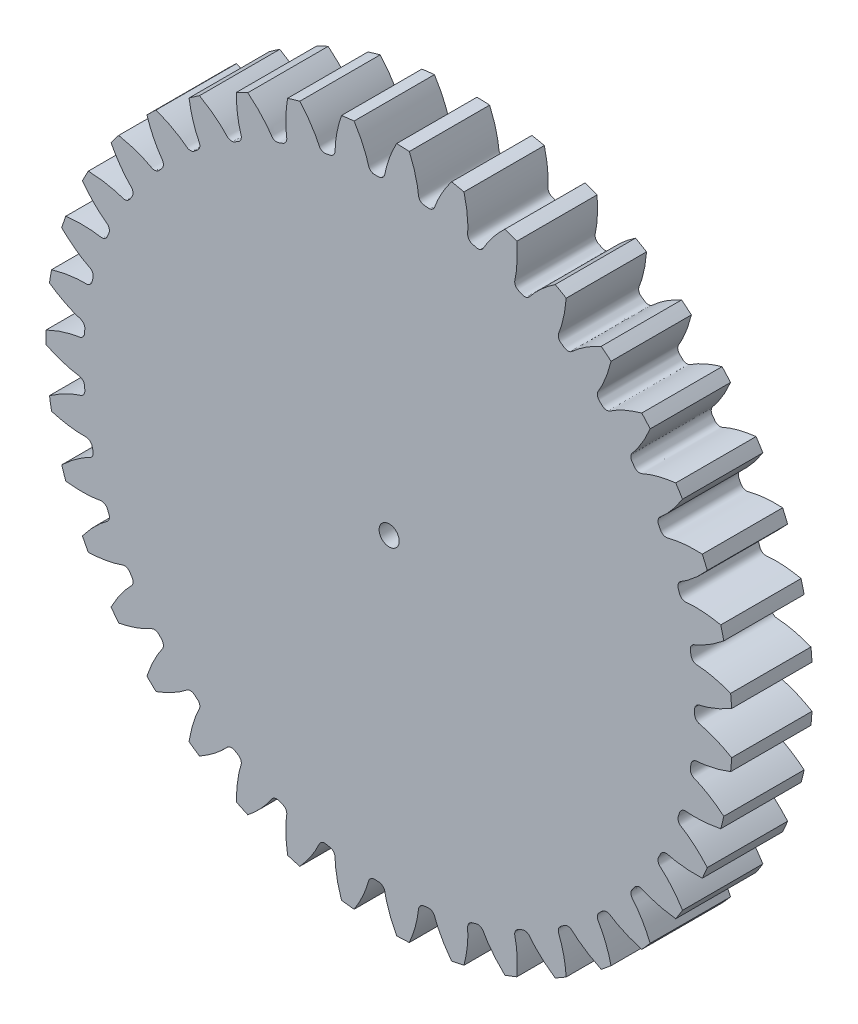
SolidWorks part; units mm, degrees
ref_plane "前视基准面" through (0, 0, 0) normal (0, 0, 1) x (1, 0, 0)
ref_plane "上视基准面" through (0, 0, 0) normal (0, 1, 0) x (1, 0, 0)
ref_plane "右视基准面" through (0, 0, 0) normal (1, 0, 0) x (0, 0, -1)
ref_axis "基准轴1" through (0, 0, 55) along (0, 0, -1)
sketch "SketchRevolveSpurGear2" plane through (0, 0, 0) normal (1, 0, 0) x (0, 0, -1)
  line L0 (0, 0) -> (1, 0) construction
  line L1 (-9.525, 0) -> (-9.525, 51.25)
  line L2 (-9.525, 51.25) -> (9.525, 51.25)
  line L3 (9.525, 51.25) -> (9.525, 0)
  line L4 (9.525, 0) -> (-9.525, 0)
revolve "SpurGear2" add sketch "SketchRevolveSpurGear2" angle 360 about L0
sketch "SketchToothSpurGear2" plane through (0, 0, 0) normal (0, 0, 1) x (1, 0, 0)
  arc A0 (51.2722, 3.2486) -> (51.2722, -3.2486) centre (0, 0) cw
  spline S0 degree 3 poles (51.2722, -3.2486) (50.9433, -3.0545) (50.5063, -2.811) (49.96, -2.5317) (49.6539, -2.3818) (49.3578, -2.2431) (49.0718, -2.1151) (48.7963, -1.9975) (48.5315, -1.8899) (48.2776, -1.7918) (48.035, -1.7028) (47.8039, -1.6225) (47.5844, -1.5505) (47.3768, -1.4864) (47.1813, -1.4298) (46.8338, -1.3346) (46.4965, -1.2659) (46.1788, -1.1645) (46.0425, -1.0887) (45.92, -0.9926) (45.8151, -0.8774) (45.7306, -0.7465) (45.6691, -0.6035) (45.6309, -0.4523) (45.6199, -0.2495) (45.6283, 0) (45.6199, 0.2495) (45.6309, 0.4523) (45.6691, 0.6035) (45.7306, 0.7465) (45.8151, 0.8774) (45.92, 0.9926) (46.0425, 1.0887) (46.1788, 1.1645) (46.4965, 1.2659) (46.8338, 1.3346) (47.1813, 1.4298) (47.3768, 1.4864) (47.5844, 1.5505) (47.8039, 1.6225) (48.035, 1.7028) (48.2776, 1.7918) (48.5315, 1.8899) (48.7963, 1.9975) (49.0718, 2.1151) (49.3578, 2.2431) (49.6539, 2.3818) (49.96, 2.5317) (50.5063, 2.811) (50.9433, 3.0545) (51.2722, 3.2486) knots 0 0 0 0 0.08292 0.108574 0.133236 0.156904 0.179579 0.201262 0.221951 0.241647 0.26035 0.27806 0.294777 0.310501 0.325231 0.338969 0.388722 0.399945 0.411168 0.422391 0.433614 0.444836 0.456059 0.467282 0.478505 0.5 0.521495 0.532718 0.543941 0.555164 0.566386 0.577609 0.588832 0.600055 0.611278 0.661031 0.674769 0.689499 0.705223 0.72194 0.73965 0.758353 0.778049 0.798738 0.820421 0.843096 0.866764 0.891426 0.91708 1 1 1 1
extrude "ToothExtrudeCutSpurGear2" cut sketch "SketchToothSpurGear2" against normal blind 9.525 and the other way blind 9.525
pattern_circular "PatternSpurGear2" count 39 every 9.231 about axis through (0, 0, 55) along (0, 0, -1) of "ToothExtrudeCutSpurGear2"
sketch "BoreRevolveSketch" plane through (0, 0, 0) normal (1, 0, 0) x (0, 0, -1)
  line L0 (0, 0) -> (1, 0) construction
  line L1 (-9.525, 0) -> (9.525, 0)
  line L2 (9.525, 0) -> (9.525, 1.5)
  line L3 (9.525, 1.5) -> (-9.525, 1.5)
  line L4 (-9.525, 1.5) -> (-9.525, 0)
  dimension "TaperSide1" = 1.5
  dimension "TaperSide2" = 1.5
revolve "BoreRevolveCut" cut sketch "BoreRevolveSketch" angle 360 about L0
sketch "AuxiliarySketchSpurGear2" plane through (0, 0, 0) normal (0, 0, 1) x (1, 0, 0)
  circle A0 centre (0, 0) radius 48.75 construction
  circle A1 centre (0, 0) radius 45.81 construction
  circle A2 centre (0, 0) radius 46.7525 construction
  circle A3 centre (0, 0) radius 51.25 construction
  circle A4 centre (0, 0) radius 45.625 construction
  dimension "PitchDiameter" = 97.5
  dimension "BaseDiameter" = 91.62
  dimension "FormDiameter" = 93.505
  dimension "MajorDiameter" = 102.5
  dimension "MinorDiameter" = 91.25
scale "缩放比例1" scale about origin uniform scaling yes scale factor 0.2
sketch "草图5" plane through (0, 0, 1.905) normal (0, 0, 1) x (1, 0, 0)
  arc A39 (0.2231, -10.2476) -> (0.6022, -10.2323) centre (0, 0) ccw
  arc A40 (1.8641, -10.0791) -> (2.2358, -10.0032) centre (0, 0) ccw
  arc A41 (3.4567, -9.6495) -> (3.8114, -9.515) centre (0, 0) ccw
  arc A42 (4.9598, -8.9701) -> (5.2884, -8.7804) centre (0, 0) ccw
  arc A43 (6.3345, -8.0583) -> (6.6284, -7.8184) centre (0, 0) ccw
  arc A44 (7.5451, -6.9378) -> (7.7967, -6.6539) centre (0, 0) ccw
  arc A45 (8.5603, -5.6377) -> (8.7631, -5.317) centre (0, 0) ccw
  arc A46 (9.3538, -4.1915) -> (9.5025, -3.8425) centre (0, 0) ccw
  arc A47 (9.9051, -2.6367) -> (9.9958, -2.2684) centre (0, 0) ccw
  arc A48 (10.1997, -1.0137) -> (10.2303, -0.6356) centre (0, 0) ccw
  arc A49 (10.2303, 0.6356) -> (10.1997, 1.0137) centre (0, 0) ccw
  arc A50 (9.9958, 2.2684) -> (9.9051, 2.6367) centre (0, 0) ccw
  arc A51 (9.5025, 3.8425) -> (9.3538, 4.1915) centre (0, 0) ccw
  arc A52 (8.7631, 5.317) -> (8.5603, 5.6377) centre (0, 0) ccw
  arc A53 (7.7967, 6.6539) -> (7.5451, 6.9378) centre (0, 0) ccw
  arc A54 (6.6284, 7.8184) -> (6.3345, 8.0583) centre (0, 0) ccw
  arc A55 (5.2884, 8.7804) -> (4.9598, 8.9701) centre (0, 0) ccw
  arc A56 (3.8114, 9.515) -> (3.4567, 9.6495) centre (0, 0) ccw
  arc A57 (2.2358, 10.0032) -> (1.8641, 10.0791) centre (0, 0) ccw
  arc A58 (0.6022, 10.2323) -> (0.2231, 10.2476) centre (0, 0) ccw
  arc A59 (-1.047, 10.1964) -> (-1.4236, 10.1507) centre (0, 0) ccw
  arc A60 (-2.669, 9.8964) -> (-3.0334, 9.7908) centre (0, 0) ccw
  arc A61 (-4.222, 9.3401) -> (-4.5647, 9.1775) centre (0, 0) ccw
  arc A62 (-5.6656, 8.5419) -> (-5.9778, 8.3264) centre (0, 0) ccw
  arc A63 (-6.9624, 7.5225) -> (-7.236, 7.2597) centre (0, 0) ccw
  arc A64 (-8.0789, 6.3082) -> (-8.3068, 6.0049) centre (0, 0) ccw
  arc A65 (-8.9862, 4.9306) -> (-9.1625, 4.5946) centre (0, 0) ccw
  arc A66 (-9.6608, 3.4252) -> (-9.7809, 3.0654) centre (0, 0) ccw
  arc A67 (-10.0851, 1.8312) -> (-10.146, 1.4567) centre (0, 0) ccw
  arc A68 (-10.2482, 0.1897) -> (-10.2482, -0.1897) centre (0, 0) ccw
  arc A69 (-10.146, -1.4567) -> (-10.0851, -1.8312) centre (0, 0) ccw
  arc A70 (-9.7809, -3.0654) -> (-9.6608, -3.4252) centre (0, 0) ccw
  arc A71 (-9.1625, -4.5946) -> (-8.9862, -4.9306) centre (0, 0) ccw
  arc A72 (-8.3068, -6.0049) -> (-8.0789, -6.3082) centre (0, 0) ccw
  arc A73 (-7.236, -7.2597) -> (-6.9624, -7.5225) centre (0, 0) ccw
  arc A74 (-5.9778, -8.3264) -> (-5.6656, -8.5419) centre (0, 0) ccw
  arc A75 (-4.5647, -9.1775) -> (-4.222, -9.3401) centre (0, 0) ccw
  arc A76 (-3.0334, -9.7908) -> (-2.669, -9.8964) centre (0, 0) ccw
  arc A77 (-1.4236, -10.1507) -> (-1.047, -10.1964) centre (0, 0) ccw
  arc A78 (0.2231, -10.2476) -> (0.6022, -10.2323) centre (0, 0) ccw
  arc A79 (1.8641, -10.0791) -> (2.2358, -10.0032) centre (0, 0) ccw
  arc A80 (3.4567, -9.6495) -> (3.8114, -9.515) centre (0, 0) ccw
  arc A81 (4.9598, -8.9701) -> (5.2884, -8.7804) centre (0, 0) ccw
  arc A82 (6.3345, -8.0583) -> (6.6284, -7.8184) centre (0, 0) ccw
  arc A83 (7.5451, -6.9378) -> (7.7967, -6.6539) centre (0, 0) ccw
  arc A84 (8.5603, -5.6377) -> (8.7631, -5.317) centre (0, 0) ccw
  arc A85 (9.3538, -4.1915) -> (9.5025, -3.8425) centre (0, 0) ccw
  arc A86 (9.9051, -2.6367) -> (9.9958, -2.2684) centre (0, 0) ccw
  arc A87 (10.1997, -1.0137) -> (10.2303, -0.6356) centre (0, 0) ccw
  arc A88 (10.2303, 0.6356) -> (10.1997, 1.0137) centre (0, 0) ccw
  arc A89 (9.9958, 2.2684) -> (9.9051, 2.6367) centre (0, 0) ccw
  arc A90 (9.5025, 3.8425) -> (9.3538, 4.1915) centre (0, 0) ccw
  arc A91 (8.7631, 5.317) -> (8.5603, 5.6377) centre (0, 0) ccw
  arc A92 (7.7967, 6.6539) -> (7.5451, 6.9378) centre (0, 0) ccw
  arc A93 (6.6284, 7.8184) -> (6.3345, 8.0583) centre (0, 0) ccw
  arc A94 (5.2884, 8.7804) -> (4.9598, 8.9701) centre (0, 0) ccw
  arc A95 (3.8114, 9.515) -> (3.4567, 9.6495) centre (0, 0) ccw
  arc A96 (2.2358, 10.0032) -> (1.8641, 10.0791) centre (0, 0) ccw
  arc A97 (0.6022, 10.2323) -> (0.2231, 10.2476) centre (0, 0) ccw
  arc A98 (-1.047, 10.1964) -> (-1.4236, 10.1507) centre (0, 0) ccw
  arc A99 (-2.669, 9.8964) -> (-3.0334, 9.7908) centre (0, 0) ccw
  arc A100 (-4.222, 9.3401) -> (-4.5647, 9.1775) centre (0, 0) ccw
  arc A101 (-5.6656, 8.5419) -> (-5.9778, 8.3264) centre (0, 0) ccw
  arc A102 (-6.9624, 7.5225) -> (-7.236, 7.2597) centre (0, 0) ccw
  arc A103 (-8.0789, 6.3082) -> (-8.3068, 6.0049) centre (0, 0) ccw
  arc A104 (-8.9862, 4.9306) -> (-9.1625, 4.5946) centre (0, 0) ccw
  arc A105 (-9.6608, 3.4252) -> (-9.7809, 3.0654) centre (0, 0) ccw
  arc A106 (-10.0851, 1.8312) -> (-10.146, 1.4567) centre (0, 0) ccw
  arc A107 (-10.2482, 0.1897) -> (-10.2482, -0.1897) centre (0, 0) ccw
  arc A108 (-10.146, -1.4567) -> (-10.0851, -1.8312) centre (0, 0) ccw
  arc A109 (-9.7809, -3.0654) -> (-9.6608, -3.4252) centre (0, 0) ccw
  arc A110 (-9.1625, -4.5946) -> (-8.9862, -4.9306) centre (0, 0) ccw
  arc A111 (-8.3068, -6.0049) -> (-8.0789, -6.3082) centre (0, 0) ccw
  arc A112 (-7.236, -7.2597) -> (-6.9624, -7.5225) centre (0, 0) ccw
  arc A113 (-5.9778, -8.3264) -> (-5.6656, -8.5419) centre (0, 0) ccw
  arc A114 (-4.5647, -9.1775) -> (-4.222, -9.3401) centre (0, 0) ccw
  arc A115 (-3.0334, -9.7908) -> (-2.669, -9.8964) centre (0, 0) ccw
  arc A116 (-1.4236, -10.1507) -> (-1.047, -10.1964) centre (0, 0) ccw
  spline S39 degree 3 poles (3980.2031, -395.6475) (-144.7935, 26.6662) (-10.7256, -27.3956) (-0.9083, -9.9635) (-0.8758, -9.9036) (-0.8457, -9.8455) (-0.8179, -9.7894) (-0.7921, -9.7353) (-0.7685, -9.6832) (-0.7469, -9.6333) (-0.7271, -9.5855) (-0.7092, -9.54) (-0.6931, -9.4967) (-0.6786, -9.4557) (-0.6657, -9.4171) (-0.6439, -9.3484) (-0.6274, -9.2816) (-0.6046, -9.2189) (-0.5883, -9.1923) (-0.5682, -9.1685) (-0.5443, -9.1485) (-0.5175, -9.1327) (-0.4884, -9.1216) (-0.4579, -9.1151) (-0.4173, -9.1146) (-0.3675, -9.1183) (-0.3175, -9.1186) (-0.2771, -9.1224) (-0.2472, -9.1313) (-0.2191, -9.1447) (-0.1936, -9.1627) (-0.1714, -9.1845) (-0.1532, -9.2098) (-0.1392, -9.2376) (-0.1215, -9.3019) (-0.1105, -9.3699) (-0.0942, -9.4401) (-0.0845, -9.4797) (-0.0734, -9.5216) (-0.0607, -9.5661) (-0.0466, -9.6129) (-0.0307, -9.6621) (-0.0132, -9.7136) (0.0062, -9.7674) (0.0275, -9.8234) (0.0508, -9.8816) (0.0761, -9.9419) (0.1036, -10.0043) (8.4863, -28.1697) (146.4675, 14.9279) (-3999.0301, -74.089) knots -21.586296 -21.586296 -21.586296 -21.586296 0.08292 0.108574 0.133236 0.156904 0.179579 0.201262 0.221951 0.241647 0.26035 0.27806 0.294777 0.310501 0.325231 0.338969 0.388722 0.399945 0.411168 0.422391 0.433614 0.444836 0.456059 0.467282 0.478505 0.5 0.521495 0.532718 0.543941 0.555164 0.566386 0.577609 0.588832 0.600055 0.611278 0.661031 0.674769 0.689499 0.705223 0.72194 0.73965 0.758353 0.778049 0.798738 0.820421 0.843096 0.866764 0.891426 0.91708 22.586117 22.586117 22.586117 22.586117 only from (-1.047, -10.1964) to (0.2231, -10.2476)
  spline S40 degree 3 poles (3992.1269, 247.9455) (-147.196, 3.0943) (-6.1922, -28.7613) (0.7018, -9.9802) (0.7241, -9.9158) (0.7445, -9.8537) (0.763, -9.7938) (0.7798, -9.7363) (0.7947, -9.6811) (0.8081, -9.6283) (0.8199, -9.578) (0.8303, -9.5302) (0.8393, -9.4849) (0.847, -9.4421) (0.8535, -9.4019) (0.8641, -9.3306) (0.8696, -9.262) (0.882, -9.1965) (0.8938, -9.1676) (0.9099, -9.141) (0.9303, -9.1174) (0.9542, -9.0974) (0.9811, -9.0818) (1.0102, -9.0705) (1.0502, -9.0635) (1.1, -9.0591) (1.1493, -9.0514) (1.1898, -9.0487) (1.2208, -9.0527) (1.2507, -9.0614) (1.2787, -9.0751) (1.3041, -9.0931) (1.3261, -9.1151) (1.3445, -9.1403) (1.3722, -9.201) (1.394, -9.2663) (1.4213, -9.333) (1.4372, -9.3704) (1.455, -9.4101) (1.4746, -9.4519) (1.4961, -9.4959) (1.5196, -9.5419) (1.5452, -9.59) (1.5729, -9.6399) (1.6029, -9.6918) (1.6352, -9.7455) (1.6699, -9.801) (1.707, -9.8581) (12.8952, -26.4436) (142.1761, 38.2297) (-3935.359, -714.6191) knots -21.586296 -21.586296 -21.586296 -21.586296 0.08292 0.108574 0.133236 0.156904 0.179579 0.201262 0.221951 0.241647 0.26035 0.27806 0.294777 0.310501 0.325231 0.338969 0.388722 0.399945 0.411168 0.422391 0.433614 0.444836 0.456059 0.467282 0.478505 0.5 0.521495 0.532718 0.543941 0.555164 0.566386 0.577609 0.588832 0.600055 0.611278 0.661031 0.674769 0.689499 0.705223 0.72194 0.73965 0.758353 0.778049 0.798738 0.820421 0.843096 0.866764 0.891426 0.91708 22.586117 22.586117 22.586117 22.586117 only from (0.6022, -10.2323) to (1.8641, -10.0791)
  spline S41 degree 3 poles (3900.6566, 885.1169) (-145.7863, -20.5577) (-1.4983, -29.3822) (2.2936, -9.7384) (2.3054, -9.6712) (2.3155, -9.6066) (2.3242, -9.5446) (2.3315, -9.4851) (2.3374, -9.4282) (2.3421, -9.374) (2.3457, -9.3224) (2.3483, -9.2736) (2.3499, -9.2274) (2.3507, -9.184) (2.3507, -9.1433) (2.3496, -9.0712) (2.344, -9.0026) (2.3458, -8.9359) (2.3528, -8.9055) (2.3645, -8.8766) (2.3808, -8.8501) (2.4012, -8.8266) (2.4253, -8.8068) (2.4522, -8.791) (2.4905, -8.7776) (2.5389, -8.7654) (2.5864, -8.7499) (2.6259, -8.7407) (2.6571, -8.7396) (2.688, -8.7435) (2.7179, -8.7524) (2.7458, -8.7662) (2.7711, -8.7843) (2.7933, -8.8063) (2.8304, -8.8617) (2.8624, -8.9227) (2.9, -8.9841) (2.9217, -9.0186) (2.9456, -9.0549) (2.9717, -9.093) (2.9999, -9.133) (3.0305, -9.1746) (3.0635, -9.2179) (3.0989, -9.2628) (3.1369, -9.3092) (3.1773, -9.357) (3.2205, -9.4062) (3.2663, -9.4566) (16.97, -24.0326) (134.2025, 60.5413) (-3769.7641, -1336.641) knots -21.586296 -21.586296 -21.586296 -21.586296 0.08292 0.108574 0.133236 0.156904 0.179579 0.201262 0.221951 0.241647 0.26035 0.27806 0.294777 0.310501 0.325231 0.338969 0.388722 0.399945 0.411168 0.422391 0.433614 0.444836 0.456059 0.467282 0.478505 0.5 0.521495 0.532718 0.543941 0.555164 0.566386 0.577609 0.588832 0.600055 0.611278 0.661031 0.674769 0.689499 0.705223 0.72194 0.73965 0.758353 0.778049 0.798738 0.820421 0.843096 0.866764 0.891426 0.91708 22.586117 22.586117 22.586117 22.586117 only from (2.2358, -10.0032) to (3.4567, -9.6495)
  spline S42 degree 3 poles (3708.1614, 1499.3642) (-140.6007, -43.6772) (3.2343, -29.242) (3.826, -9.2443) (3.8269, -9.1762) (3.8266, -9.1108) (3.8252, -9.0481) (3.8228, -8.9883) (3.8195, -8.9312) (3.8155, -8.8769) (3.8108, -8.8254) (3.8055, -8.7768) (3.7997, -8.731) (3.7934, -8.688) (3.7869, -8.6478) (3.7743, -8.5768) (3.7578, -8.51) (3.7489, -8.4439) (3.7509, -8.4128) (3.7577, -8.3824) (3.7696, -8.3536) (3.786, -8.3271) (3.8066, -8.3037) (3.8306, -8.2838) (3.8663, -8.2645) (3.9121, -8.2446) (3.9565, -8.2217) (3.994, -8.2063) (4.0246, -8.2002) (4.0558, -8.1991) (4.0867, -8.2031) (4.1165, -8.2122) (4.1443, -8.2261) (4.1697, -8.2442) (4.2153, -8.2929) (4.2566, -8.348) (4.3036, -8.4026) (4.3306, -8.4331) (4.36, -8.4651) (4.3918, -8.4986) (4.4261, -8.5335) (4.463, -8.5697) (4.5025, -8.6071) (4.5447, -8.6457) (4.5895, -8.6854) (4.6372, -8.7261) (4.6876, -8.7678) (4.7409, -8.8102) (20.6054, -20.9992) (122.7531, 81.2849) (-3506.5344, -1924.0445) knots -21.586296 -21.586296 -21.586296 -21.586296 0.08292 0.108574 0.133236 0.156904 0.179579 0.201262 0.221951 0.241647 0.26035 0.27806 0.294777 0.310501 0.325231 0.338969 0.388722 0.399945 0.411168 0.422391 0.433614 0.444836 0.456059 0.467282 0.478505 0.5 0.521495 0.532718 0.543941 0.555164 0.566386 0.577609 0.588832 0.600055 0.611278 0.661031 0.674769 0.689499 0.705223 0.72194 0.73965 0.758353 0.778049 0.798738 0.820421 0.843096 0.866764 0.891426 0.91708 22.586117 22.586117 22.586117 22.586117 only from (3.8114, -9.515) to (4.9598, -8.9701)
  spline S43 degree 3 poles (3419.6267, 2074.7787) (-131.7736, -65.6655) (7.8832, -28.3445) (5.2594, -8.5109) (5.2493, -8.4435) (5.2385, -8.379) (5.227, -8.3174) (5.2151, -8.2587) (5.2027, -8.2028) (5.19, -8.1499) (5.1771, -8.0999) (5.1641, -8.0527) (5.151, -8.0084) (5.138, -7.9669) (5.1251, -7.9283) (5.1013, -7.8603) (5.0742, -7.797) (5.0548, -7.7332) (5.0518, -7.7021) (5.0537, -7.6711) (5.0608, -7.6407) (5.0727, -7.6119) (5.0893, -7.5856) (5.1098, -7.5621) (5.1419, -7.5372) (5.184, -7.5103) (5.2241, -7.4805) (5.2587, -7.4593) (5.2879, -7.4484) (5.3185, -7.4423) (5.3496, -7.4413) (5.3805, -7.4455) (5.4102, -7.4548) (5.4382, -7.4686) (5.491, -7.5093) (5.5406, -7.5571) (5.5957, -7.6035) (5.6273, -7.6292) (5.6614, -7.6561) (5.6982, -7.684) (5.7377, -7.713) (5.7799, -7.7428) (5.8249, -7.7734) (5.8727, -7.8048) (5.9233, -7.8368) (5.9769, -7.8693) (6.0334, -7.9023) (6.0928, -7.9356) (23.707, -17.4219) (108.1245, 99.9232) (-3152.4872, -2461.6163) knots -21.586296 -21.586296 -21.586296 -21.586296 0.08292 0.108574 0.133236 0.156904 0.179579 0.201262 0.221951 0.241647 0.26035 0.27806 0.294777 0.310501 0.325231 0.338969 0.388722 0.399945 0.411168 0.422391 0.433614 0.444836 0.456059 0.467282 0.478505 0.5 0.521495 0.532718 0.543941 0.555164 0.566386 0.577609 0.588832 0.600055 0.611278 0.661031 0.674769 0.689499 0.705223 0.72194 0.73965 0.758353 0.778049 0.798738 0.820421 0.843096 0.866764 0.891426 0.91708 22.586117 22.586117 22.586117 22.586117 only from (5.2884, -8.7804) to (6.3345, -8.0583)
  spline S44 degree 3 poles (3042.5256, 2596.4576) (-119.5337, -85.9532) (12.3279, -26.7129) (6.5565, -7.557) (6.5357, -7.4921) (6.5147, -7.4302) (6.4936, -7.3712) (6.4723, -7.3151) (6.4512, -7.262) (6.4302, -7.2118) (6.4094, -7.1645) (6.3889, -7.12) (6.3689, -7.0784) (6.3494, -7.0396) (6.3305, -7.0035) (6.2961, -6.9402) (6.2593, -6.8821) (6.2299, -6.8222) (6.2219, -6.792) (6.2188, -6.761) (6.2209, -6.73) (6.2281, -6.6996) (6.2402, -6.6709) (6.2567, -6.6445) (6.2844, -6.6148) (6.3216, -6.5815) (6.3564, -6.5457) (6.3872, -6.5192) (6.4143, -6.5037) (6.4434, -6.4928) (6.474, -6.4868) (6.5052, -6.486) (6.536, -6.4904) (6.5658, -6.4995) (6.6244, -6.5313) (6.6811, -6.5704) (6.743, -6.6074) (6.7782, -6.6277) (6.8162, -6.6488) (6.857, -6.6705) (6.9006, -6.6927) (6.9471, -6.7153) (6.9964, -6.7384) (7.0486, -6.7617) (7.1037, -6.7851) (7.1618, -6.8086) (7.2229, -6.8321) (7.2869, -6.8555) (26.1947, -13.3934) (90.6955, 115.9736) (-2716.7923, -2935.4335) knots -21.586296 -21.586296 -21.586296 -21.586296 0.08292 0.108574 0.133236 0.156904 0.179579 0.201262 0.221951 0.241647 0.26035 0.27806 0.294777 0.310501 0.325231 0.338969 0.388722 0.399945 0.411168 0.422391 0.433614 0.444836 0.456059 0.467282 0.478505 0.5 0.521495 0.532718 0.543941 0.555164 0.566386 0.577609 0.588832 0.600055 0.611278 0.661031 0.674769 0.689499 0.705223 0.72194 0.73965 0.758353 0.778049 0.798738 0.820421 0.843096 0.866764 0.891426 0.91708 22.586117 22.586117 22.586117 22.586117 only from (6.6284, -7.8184) to (7.5451, -6.9378)
  spline S45 degree 3 poles (2586.6246, 3050.8896) (-104.1979, -104.0146) (16.4533, -24.3895) (7.6839, -6.4074) (7.6529, -6.3467) (7.6222, -6.2889) (7.5919, -6.2341) (7.562, -6.1822) (7.5326, -6.1332) (7.5038, -6.087) (7.4757, -6.0436) (7.4483, -6.003) (7.4219, -5.9651) (7.3964, -5.9299) (7.372, -5.8974) (7.3278, -5.8404) (7.2822, -5.7889) (7.2435, -5.7345) (7.2309, -5.706) (7.2228, -5.6759) (7.2199, -5.6449) (7.2221, -5.6138) (7.2295, -5.5836) (7.2415, -5.5548) (7.2641, -5.5211) (7.2954, -5.4822) (7.3241, -5.4413) (7.3502, -5.4102) (7.3745, -5.3906) (7.4015, -5.3751) (7.4307, -5.3643) (7.4613, -5.3585) (7.4925, -5.3579) (7.5234, -5.3621) (7.5864, -5.3841) (7.6485, -5.4136) (7.7155, -5.4402) (7.7536, -5.4546) (7.7945, -5.4693) (7.8382, -5.4841) (7.8848, -5.4991) (7.9343, -5.514) (7.9867, -5.5288) (8.042, -5.5434) (8.1002, -5.5577) (8.1613, -5.5716) (8.2253, -5.585) (8.2922, -5.5978) (28.004, -9.0181) (70.9175, 129.0204) (-2210.7339, -3333.2246) knots -21.586296 -21.586296 -21.586296 -21.586296 0.08292 0.108574 0.133236 0.156904 0.179579 0.201262 0.221951 0.241647 0.26035 0.27806 0.294777 0.310501 0.325231 0.338969 0.388722 0.399945 0.411168 0.422391 0.433614 0.444836 0.456059 0.467282 0.478505 0.5 0.521495 0.532718 0.543941 0.555164 0.566386 0.577609 0.588832 0.600055 0.611278 0.661031 0.674769 0.689499 0.705223 0.72194 0.73965 0.758353 0.778049 0.798738 0.820421 0.843096 0.866764 0.891426 0.91708 22.586117 22.586117 22.586117 22.586117 only from (7.7967, -6.6539) to (8.5603, -5.6377)
  spline S46 degree 3 poles (2063.7314, 3426.3051) (-86.1635, -119.3822) (20.1526, -21.4343) (8.6122, -5.0918) (8.5719, -5.0369) (8.5323, -4.9848) (8.4936, -4.9355) (8.4557, -4.8891) (8.4188, -4.8454) (8.383, -4.8045) (8.3483, -4.7661) (8.3148, -4.7304) (8.2827, -4.6973) (8.2519, -4.6666) (8.2225, -4.6385) (8.1698, -4.5893) (8.1165, -4.5458) (8.0696, -4.4983) (8.0525, -4.4722) (8.0398, -4.4438) (8.0319, -4.4136) (8.0291, -4.3826) (8.0315, -4.3516) (8.0388, -4.3212) (8.0557, -4.2843) (8.0804, -4.2409) (8.1021, -4.1959) (8.1229, -4.1611) (8.1437, -4.1378) (8.1679, -4.1182) (8.195, -4.1029) (8.2243, -4.0922) (8.2549, -4.0866) (8.2861, -4.0858) (8.3518, -4.0974) (8.4179, -4.1166) (8.4883, -4.1321) (8.5282, -4.1402) (8.5709, -4.1481) (8.6164, -4.1558) (8.6648, -4.163) (8.7161, -4.1698) (8.7702, -4.1761) (8.8271, -4.1816) (8.8868, -4.1864) (8.9493, -4.1903) (9.0147, -4.1933) (9.0828, -4.1952) (29.0879, -4.4091) (49.3029, 138.7256) (-1647.4187, -3644.6869) knots -21.586296 -21.586296 -21.586296 -21.586296 0.08292 0.108574 0.133236 0.156904 0.179579 0.201262 0.221951 0.241647 0.26035 0.27806 0.294777 0.310501 0.325231 0.338969 0.388722 0.399945 0.411168 0.422391 0.433614 0.444836 0.456059 0.467282 0.478505 0.5 0.521495 0.532718 0.543941 0.555164 0.566386 0.577609 0.588832 0.600055 0.611278 0.661031 0.674769 0.689499 0.705223 0.72194 0.73965 0.758353 0.778049 0.798738 0.820421 0.843096 0.866764 0.891426 0.91708 22.586117 22.586117 22.586117 22.586117 only from (8.7631, -5.317) to (9.3538, -4.1915)
  spline S47 degree 3 poles (1487.3886, 3712.9812) (-65.8974, -131.6578) (23.3299, -17.9241) (9.3174, -3.6444) (9.2689, -3.5966) (9.2215, -3.5515) (9.1753, -3.5092) (9.1305, -3.4694) (9.0871, -3.4322) (9.0451, -3.3975) (9.0047, -3.3653) (8.966, -3.3354) (8.9289, -3.3078) (8.8936, -3.2825) (8.8601, -3.2594) (8.8002, -3.2193) (8.7405, -3.1849) (8.6867, -3.1456) (8.6656, -3.1226) (8.6485, -3.0966) (8.6359, -3.0681) (8.6281, -3.0379) (8.6255, -3.0069) (8.6279, -2.9758) (8.6386, -2.9366) (8.656, -2.8898) (8.6702, -2.8419) (8.6852, -2.8042) (8.702, -2.7779) (8.7227, -2.7547) (8.747, -2.7352) (8.7742, -2.72) (8.8035, -2.7095) (8.8342, -2.7037) (8.9009, -2.7046) (8.9692, -2.713) (9.0412, -2.7169) (9.0819, -2.7186) (9.1253, -2.7195) (9.1715, -2.7198) (9.2204, -2.7192) (9.2721, -2.7177) (9.3265, -2.7151) (9.3835, -2.7115) (9.4432, -2.7066) (9.5056, -2.7005) (9.5706, -2.6929) (9.6381, -2.6839) (29.4185, 0.314) (26.4113, 144.8379) (-1041.4362, -3861.7537) knots -21.586296 -21.586296 -21.586296 -21.586296 0.08292 0.108574 0.133236 0.156904 0.179579 0.201262 0.221951 0.241647 0.26035 0.27806 0.294777 0.310501 0.325231 0.338969 0.388722 0.399945 0.411168 0.422391 0.433614 0.444836 0.456059 0.467282 0.478505 0.5 0.521495 0.532718 0.543941 0.555164 0.566386 0.577609 0.588832 0.600055 0.611278 0.661031 0.674769 0.689499 0.705223 0.72194 0.73965 0.758353 0.778049 0.798738 0.820421 0.843096 0.866764 0.891426 0.91708 22.586117 22.586117 22.586117 22.586117 only from (9.5025, -3.8425) to (9.9051, -2.6367)
  spline S48 degree 3 poles (872.5232, 3903.4929) (-43.9247, -140.5236) (25.903, -13.9496) (9.7814, -2.1026) (9.7258, -2.0632) (9.6718, -2.0263) (9.6194, -1.9919) (9.5688, -1.9598) (9.52, -1.9301) (9.473, -1.9026) (9.428, -1.8772) (9.3849, -1.854) (9.3439, -1.8327) (9.305, -1.8134) (9.2682, -1.7959) (9.2027, -1.766) (9.1383, -1.7416) (9.0788, -1.7114) (9.0543, -1.6921) (9.0332, -1.6692) (9.0162, -1.6431) (9.0037, -1.6145) (8.9962, -1.5843) (8.9935, -1.5532) (8.9978, -1.5129) (9.0075, -1.4639) (9.0138, -1.4143) (9.0225, -1.3747) (9.0349, -1.346) (9.0516, -1.3198) (9.0725, -1.2966) (9.0969, -1.2773) (9.1242, -1.2622) (9.1535, -1.2516) (9.2195, -1.2418) (9.2883, -1.2391) (9.3599, -1.2314) (9.4003, -1.2265) (9.4434, -1.2205) (9.489, -1.2134) (9.5372, -1.2049) (9.588, -1.1951) (9.6412, -1.1839) (9.697, -1.1712) (9.7551, -1.1568) (9.8157, -1.1407) (9.8786, -1.1228) (9.9438, -1.1031) (28.9872, 5.029) (2.8356, 147.1989) (-408.481, -3978.8031) knots -21.586296 -21.586296 -21.586296 -21.586296 0.08292 0.108574 0.133236 0.156904 0.179579 0.201262 0.221951 0.241647 0.26035 0.27806 0.294777 0.310501 0.325231 0.338969 0.388722 0.399945 0.411168 0.422391 0.433614 0.444836 0.456059 0.467282 0.478505 0.5 0.521495 0.532718 0.543941 0.555164 0.566386 0.577609 0.588832 0.600055 0.611278 0.661031 0.674769 0.689499 0.705223 0.72194 0.73965 0.758353 0.778049 0.798738 0.820421 0.843096 0.866764 0.891426 0.91708 22.586117 22.586117 22.586117 22.586117 only from (9.9958, -2.2684) to (10.1997, -1.0137)
  spline S49 degree 3 poles (235.06, 3992.9063) (-20.8143, -145.7498) (27.8052, -9.6138) (9.992, -0.5063) (9.9308, -0.4764) (9.8716, -0.4486) (9.8144, -0.423) (9.7593, -0.3995) (9.7063, -0.378) (9.6555, -0.3584) (9.607, -0.3406) (9.5608, -0.3245) (9.5169, -0.3101) (9.4754, -0.2973) (9.4363, -0.286) (9.3668, -0.2669) (9.2993, -0.2532) (9.2358, -0.2329) (9.2085, -0.2177) (9.184, -0.1985) (9.163, -0.1755) (9.1461, -0.1493) (9.1338, -0.1207) (9.1262, -0.0905) (9.124, -0.0499) (9.1257, 0) (9.124, 0.0499) (9.1262, 0.0905) (9.1338, 0.1207) (9.1461, 0.1493) (9.163, 0.1755) (9.184, 0.1985) (9.2085, 0.2177) (9.2358, 0.2329) (9.2993, 0.2532) (9.3668, 0.2669) (9.4363, 0.286) (9.4754, 0.2973) (9.5169, 0.3101) (9.5608, 0.3245) (9.607, 0.3406) (9.6555, 0.3584) (9.7063, 0.378) (9.7593, 0.3995) (9.8144, 0.423) (9.8716, 0.4486) (9.9308, 0.4764) (9.992, 0.5063) (27.8051, 9.6137) (-20.8135, 145.7476) (235.0536, -3992.8036) knots -21.586296 -21.586296 -21.586296 -21.586296 0.08292 0.108574 0.133236 0.156904 0.179579 0.201262 0.221951 0.241647 0.26035 0.27806 0.294777 0.310501 0.325231 0.338969 0.388722 0.399945 0.411168 0.422391 0.433614 0.444836 0.456059 0.467282 0.478505 0.5 0.521495 0.532718 0.543941 0.555164 0.566386 0.577609 0.588832 0.600055 0.611278 0.661031 0.674769 0.689499 0.705223 0.72194 0.73965 0.758353 0.778049 0.798738 0.820421 0.843096 0.866764 0.891426 0.91708 22.586117 22.586117 22.586117 22.586117 only from (10.2303, -0.6356) to (10.2303, 0.6356)
  spline S50 degree 3 poles (-408.4912, 3978.9055) (2.8352, -147.2013) (28.9873, -5.029) (9.9438, 1.1031) (9.8786, 1.1228) (9.8157, 1.1407) (9.7551, 1.1568) (9.697, 1.1712) (9.6412, 1.1839) (9.588, 1.1951) (9.5372, 1.2049) (9.489, 1.2134) (9.4434, 1.2205) (9.4003, 1.2265) (9.3599, 1.2314) (9.2883, 1.2391) (9.2195, 1.2418) (9.1535, 1.2516) (9.1242, 1.2622) (9.0969, 1.2773) (9.0725, 1.2966) (9.0516, 1.3198) (9.0349, 1.346) (9.0225, 1.3747) (9.0138, 1.4143) (9.0075, 1.4639) (8.9978, 1.5129) (8.9935, 1.5532) (8.9962, 1.5843) (9.0037, 1.6145) (9.0162, 1.6431) (9.0332, 1.6692) (9.0543, 1.6921) (9.0788, 1.7114) (9.1383, 1.7416) (9.2027, 1.766) (9.2682, 1.7959) (9.305, 1.8134) (9.3439, 1.8327) (9.3849, 1.854) (9.428, 1.8772) (9.473, 1.9026) (9.52, 1.9301) (9.5688, 1.9598) (9.6194, 1.9919) (9.6718, 2.0263) (9.7258, 2.0632) (9.7814, 2.1026) (25.9029, 13.9495) (-43.9235, 140.5215) (872.5005, -3903.3926) knots -21.586296 -21.586296 -21.586296 -21.586296 0.08292 0.108574 0.133236 0.156904 0.179579 0.201262 0.221951 0.241647 0.26035 0.27806 0.294777 0.310501 0.325231 0.338969 0.388722 0.399945 0.411168 0.422391 0.433614 0.444836 0.456059 0.467282 0.478505 0.5 0.521495 0.532718 0.543941 0.555164 0.566386 0.577609 0.588832 0.600055 0.611278 0.661031 0.674769 0.689499 0.705223 0.72194 0.73965 0.758353 0.778049 0.798738 0.820421 0.843096 0.866764 0.891426 0.91708 22.586117 22.586117 22.586117 22.586117 only from (10.1997, 1.0137) to (9.9958, 2.2684)
  spline S51 degree 3 poles (-1041.4627, 3861.8531) (26.4112, -144.8403) (29.4187, -0.314) (9.6381, 2.6839) (9.5706, 2.6929) (9.5056, 2.7005) (9.4432, 2.7066) (9.3835, 2.7115) (9.3265, 2.7151) (9.2721, 2.7177) (9.2204, 2.7192) (9.1715, 2.7198) (9.1253, 2.7195) (9.0819, 2.7186) (9.0412, 2.7169) (8.9692, 2.713) (8.9009, 2.7046) (8.8342, 2.7037) (8.8035, 2.7095) (8.7742, 2.72) (8.747, 2.7352) (8.7227, 2.7547) (8.702, 2.7779) (8.6852, 2.8042) (8.6702, 2.8419) (8.656, 2.8898) (8.6386, 2.9366) (8.6279, 2.9758) (8.6255, 3.0069) (8.6281, 3.0379) (8.6359, 3.0681) (8.6485, 3.0966) (8.6656, 3.1226) (8.6867, 3.1456) (8.7405, 3.1849) (8.8002, 3.2193) (8.8601, 3.2594) (8.8936, 3.2825) (8.9289, 3.3078) (8.966, 3.3354) (9.0047, 3.3653) (9.0451, 3.3975) (9.0871, 3.4322) (9.1305, 3.4694) (9.1753, 3.5092) (9.2215, 3.5515) (9.2689, 3.5966) (9.3174, 3.6444) (23.3298, 17.924) (-65.8959, 131.6559) (1487.35, -3712.8857) knots -21.586296 -21.586296 -21.586296 -21.586296 0.08292 0.108574 0.133236 0.156904 0.179579 0.201262 0.221951 0.241647 0.26035 0.27806 0.294777 0.310501 0.325231 0.338969 0.388722 0.399945 0.411168 0.422391 0.433614 0.444836 0.456059 0.467282 0.478505 0.5 0.521495 0.532718 0.543941 0.555164 0.566386 0.577609 0.588832 0.600055 0.611278 0.661031 0.674769 0.689499 0.705223 0.72194 0.73965 0.758353 0.778049 0.798738 0.820421 0.843096 0.866764 0.891426 0.91708 22.586117 22.586117 22.586117 22.586117 only from (9.9051, 2.6367) to (9.5025, 3.8425)
  spline S52 degree 3 poles (-1647.4608, 3644.7808) (49.3032, -138.728) (29.0881, 4.4091) (9.0828, 4.1952) (9.0147, 4.1933) (8.9493, 4.1903) (8.8868, 4.1864) (8.8271, 4.1816) (8.7702, 4.1761) (8.7161, 4.1698) (8.6648, 4.163) (8.6164, 4.1558) (8.5709, 4.1481) (8.5282, 4.1402) (8.4883, 4.1321) (8.4179, 4.1166) (8.3518, 4.0974) (8.2861, 4.0858) (8.2549, 4.0866) (8.2243, 4.0922) (8.195, 4.1029) (8.1679, 4.1182) (8.1437, 4.1378) (8.1229, 4.1611) (8.1021, 4.1959) (8.0804, 4.2409) (8.0557, 4.2843) (8.0388, 4.3212) (8.0315, 4.3516) (8.0291, 4.3826) (8.0319, 4.4136) (8.0398, 4.4438) (8.0525, 4.4722) (8.0696, 4.4983) (8.1165, 4.5458) (8.1698, 4.5893) (8.2225, 4.6385) (8.2519, 4.6666) (8.2827, 4.6973) (8.3148, 4.7304) (8.3483, 4.7661) (8.383, 4.8045) (8.4188, 4.8454) (8.4557, 4.8891) (8.4936, 4.9355) (8.5323, 4.9848) (8.5719, 5.0369) (8.6122, 5.0918) (20.1525, 21.4342) (-86.1617, 119.3806) (2063.678, -3426.2171) knots -21.586296 -21.586296 -21.586296 -21.586296 0.08292 0.108574 0.133236 0.156904 0.179579 0.201262 0.221951 0.241647 0.26035 0.27806 0.294777 0.310501 0.325231 0.338969 0.388722 0.399945 0.411168 0.422391 0.433614 0.444836 0.456059 0.467282 0.478505 0.5 0.521495 0.532718 0.543941 0.555164 0.566386 0.577609 0.588832 0.600055 0.611278 0.661031 0.674769 0.689499 0.705223 0.72194 0.73965 0.758353 0.778049 0.798738 0.820421 0.843096 0.866764 0.891426 0.91708 22.586117 22.586117 22.586117 22.586117 only from (9.3538, 4.1915) to (8.7631, 5.317)
  spline S53 degree 3 poles (-2210.7906, 3333.3105) (70.9183, -129.0227) (28.0041, 9.0181) (8.2922, 5.5978) (8.2253, 5.585) (8.1613, 5.5716) (8.1002, 5.5577) (8.042, 5.5434) (7.9867, 5.5288) (7.9343, 5.514) (7.8848, 5.4991) (7.8382, 5.4841) (7.7945, 5.4693) (7.7536, 5.4546) (7.7155, 5.4402) (7.6485, 5.4136) (7.5864, 5.3841) (7.5234, 5.3621) (7.4925, 5.3579) (7.4613, 5.3585) (7.4307, 5.3643) (7.4015, 5.3751) (7.3745, 5.3906) (7.3502, 5.4102) (7.3241, 5.4413) (7.2954, 5.4822) (7.2641, 5.5211) (7.2415, 5.5548) (7.2295, 5.5836) (7.2221, 5.6138) (7.2199, 5.6449) (7.2228, 5.6759) (7.2309, 5.706) (7.2435, 5.7345) (7.2822, 5.7889) (7.3278, 5.8404) (7.372, 5.8974) (7.3964, 5.9299) (7.4219, 5.9651) (7.4483, 6.003) (7.4757, 6.0436) (7.5038, 6.087) (7.5326, 6.1332) (7.562, 6.1822) (7.5919, 6.2341) (7.6222, 6.2889) (7.6529, 6.3467) (7.6839, 6.4074) (16.4532, 24.3893) (-104.1959, 104.0133) (2586.5578, -3050.8113) knots -21.586296 -21.586296 -21.586296 -21.586296 0.08292 0.108574 0.133236 0.156904 0.179579 0.201262 0.221951 0.241647 0.26035 0.27806 0.294777 0.310501 0.325231 0.338969 0.388722 0.399945 0.411168 0.422391 0.433614 0.444836 0.456059 0.467282 0.478505 0.5 0.521495 0.532718 0.543941 0.555164 0.566386 0.577609 0.588832 0.600055 0.611278 0.661031 0.674769 0.689499 0.705223 0.72194 0.73965 0.758353 0.778049 0.798738 0.820421 0.843096 0.866764 0.891426 0.91708 22.586117 22.586117 22.586117 22.586117 only from (8.5603, 5.6377) to (7.7967, 6.6539)
  spline S54 degree 3 poles (-2716.862, 2935.5093) (90.6966, -115.9758) (26.1949, 13.3935) (7.2869, 6.8555) (7.2229, 6.8321) (7.1618, 6.8086) (7.1037, 6.7851) (7.0486, 6.7617) (6.9964, 6.7384) (6.9471, 6.7153) (6.9006, 6.6927) (6.857, 6.6705) (6.8162, 6.6488) (6.7782, 6.6277) (6.743, 6.6074) (6.6811, 6.5704) (6.6244, 6.5313) (6.5658, 6.4995) (6.536, 6.4904) (6.5052, 6.486) (6.474, 6.4868) (6.4434, 6.4928) (6.4143, 6.5037) (6.3872, 6.5192) (6.3564, 6.5457) (6.3216, 6.5815) (6.2844, 6.6148) (6.2567, 6.6445) (6.2402, 6.6709) (6.2281, 6.6996) (6.2209, 6.73) (6.2188, 6.761) (6.2219, 6.792) (6.2299, 6.8222) (6.2593, 6.8821) (6.2961, 6.9402) (6.3305, 7.0035) (6.3494, 7.0396) (6.3689, 7.0784) (6.3889, 7.12) (6.4094, 7.1645) (6.4302, 7.2118) (6.4512, 7.262) (6.4723, 7.3151) (6.4936, 7.3712) (6.5147, 7.4302) (6.5357, 7.4921) (6.5565, 7.557) (12.3278, 26.7128) (-119.5315, 85.9522) (3042.4471, -2596.391) knots -21.586296 -21.586296 -21.586296 -21.586296 0.08292 0.108574 0.133236 0.156904 0.179579 0.201262 0.221951 0.241647 0.26035 0.27806 0.294777 0.310501 0.325231 0.338969 0.388722 0.399945 0.411168 0.422391 0.433614 0.444836 0.456059 0.467282 0.478505 0.5 0.521495 0.532718 0.543941 0.555164 0.566386 0.577609 0.588832 0.600055 0.611278 0.661031 0.674769 0.689499 0.705223 0.72194 0.73965 0.758353 0.778049 0.798738 0.820421 0.843096 0.866764 0.891426 0.91708 22.586117 22.586117 22.586117 22.586117 only from (7.5451, 6.9378) to (6.6284, 7.8184)
  spline S55 degree 3 poles (-3152.5682, 2461.6799) (108.1259, -99.9252) (23.7072, 17.422) (6.0928, 7.9356) (6.0334, 7.9023) (5.9769, 7.8693) (5.9233, 7.8368) (5.8727, 7.8048) (5.8249, 7.7734) (5.7799, 7.7428) (5.7377, 7.713) (5.6982, 7.684) (5.6614, 7.6561) (5.6273, 7.6292) (5.5957, 7.6035) (5.5406, 7.5571) (5.491, 7.5093) (5.4382, 7.4686) (5.4102, 7.4548) (5.3805, 7.4455) (5.3496, 7.4413) (5.3185, 7.4423) (5.2879, 7.4484) (5.2587, 7.4593) (5.2241, 7.4805) (5.184, 7.5103) (5.1419, 7.5372) (5.1098, 7.5621) (5.0893, 7.5856) (5.0727, 7.6119) (5.0608, 7.6407) (5.0537, 7.6711) (5.0518, 7.7021) (5.0548, 7.7332) (5.0742, 7.797) (5.1013, 7.8603) (5.1251, 7.9283) (5.138, 7.9669) (5.151, 8.0084) (5.1641, 8.0527) (5.1771, 8.0999) (5.19, 8.1499) (5.2027, 8.2028) (5.2151, 8.2587) (5.227, 8.3174) (5.2385, 8.379) (5.2493, 8.4435) (5.2594, 8.5109) (7.8832, 28.3444) (-131.7713, 65.6649) (3419.5386, -2074.7256) knots -21.586296 -21.586296 -21.586296 -21.586296 0.08292 0.108574 0.133236 0.156904 0.179579 0.201262 0.221951 0.241647 0.26035 0.27806 0.294777 0.310501 0.325231 0.338969 0.388722 0.399945 0.411168 0.422391 0.433614 0.444836 0.456059 0.467282 0.478505 0.5 0.521495 0.532718 0.543941 0.555164 0.566386 0.577609 0.588832 0.600055 0.611278 0.661031 0.674769 0.689499 0.705223 0.72194 0.73965 0.758353 0.778049 0.798738 0.820421 0.843096 0.866764 0.891426 0.91708 22.586117 22.586117 22.586117 22.586117 only from (6.3345, 8.0583) to (5.2884, 8.7804)
  spline S56 degree 3 poles (-3506.6245, 1924.0943) (122.7548, -81.2865) (20.6055, 20.9993) (4.7409, 8.8102) (4.6876, 8.7678) (4.6372, 8.7261) (4.5895, 8.6854) (4.5447, 8.6457) (4.5025, 8.6071) (4.463, 8.5697) (4.4261, 8.5335) (4.3918, 8.4986) (4.36, 8.4651) (4.3306, 8.4331) (4.3036, 8.4026) (4.2566, 8.348) (4.2153, 8.2929) (4.1697, 8.2442) (4.1443, 8.2261) (4.1165, 8.2122) (4.0867, 8.2031) (4.0558, 8.1991) (4.0246, 8.2002) (3.994, 8.2063) (3.9565, 8.2217) (3.9121, 8.2446) (3.8663, 8.2645) (3.8306, 8.2838) (3.8066, 8.3037) (3.786, 8.3271) (3.7696, 8.3536) (3.7577, 8.3824) (3.7509, 8.4128) (3.7489, 8.4439) (3.7578, 8.51) (3.7743, 8.5768) (3.7869, 8.6478) (3.7934, 8.688) (3.7997, 8.731) (3.8055, 8.7768) (3.8108, 8.8254) (3.8155, 8.8769) (3.8195, 8.9312) (3.8228, 8.9883) (3.8252, 9.0481) (3.8266, 9.1108) (3.8269, 9.1762) (3.826, 9.2443) (3.2343, 29.2419) (-140.5983, 43.677) (3708.0659, -1499.3259) knots -21.586296 -21.586296 -21.586296 -21.586296 0.08292 0.108574 0.133236 0.156904 0.179579 0.201262 0.221951 0.241647 0.26035 0.27806 0.294777 0.310501 0.325231 0.338969 0.388722 0.399945 0.411168 0.422391 0.433614 0.444836 0.456059 0.467282 0.478505 0.5 0.521495 0.532718 0.543941 0.555164 0.566386 0.577609 0.588832 0.600055 0.611278 0.661031 0.674769 0.689499 0.705223 0.72194 0.73965 0.758353 0.778049 0.798738 0.820421 0.843096 0.866764 0.891426 0.91708 22.586117 22.586117 22.586117 22.586117 only from (4.9598, 8.9701) to (3.8114, 9.515)
  spline S57 degree 3 poles (-3769.861, 1336.6756) (134.2045, -60.5426) (16.9701, 24.0327) (3.2663, 9.4566) (3.2205, 9.4062) (3.1773, 9.357) (3.1369, 9.3092) (3.0989, 9.2628) (3.0635, 9.2179) (3.0305, 9.1746) (2.9999, 9.133) (2.9717, 9.093) (2.9456, 9.0549) (2.9217, 9.0186) (2.9, 8.9841) (2.8624, 8.9227) (2.8304, 8.8617) (2.7933, 8.8063) (2.7711, 8.7843) (2.7458, 8.7662) (2.7179, 8.7524) (2.688, 8.7435) (2.6571, 8.7396) (2.6259, 8.7407) (2.5864, 8.7499) (2.5389, 8.7654) (2.4905, 8.7776) (2.4522, 8.791) (2.4253, 8.8068) (2.4012, 8.8266) (2.3808, 8.8501) (2.3645, 8.8766) (2.3528, 8.9055) (2.3458, 8.9359) (2.344, 9.0026) (2.3496, 9.0712) (2.3507, 9.1433) (2.3507, 9.184) (2.3499, 9.2274) (2.3483, 9.2736) (2.3457, 9.3224) (2.3421, 9.374) (2.3374, 9.4282) (2.3315, 9.4851) (2.3242, 9.5446) (2.3155, 9.6066) (2.3054, 9.6712) (2.2936, 9.7384) (-1.4983, 29.382) (-145.7839, 20.5578) (3900.5562, -885.0944) knots -21.586296 -21.586296 -21.586296 -21.586296 0.08292 0.108574 0.133236 0.156904 0.179579 0.201262 0.221951 0.241647 0.26035 0.27806 0.294777 0.310501 0.325231 0.338969 0.388722 0.399945 0.411168 0.422391 0.433614 0.444836 0.456059 0.467282 0.478505 0.5 0.521495 0.532718 0.543941 0.555164 0.566386 0.577609 0.588832 0.600055 0.611278 0.661031 0.674769 0.689499 0.705223 0.72194 0.73965 0.758353 0.778049 0.798738 0.820421 0.843096 0.866764 0.891426 0.91708 22.586117 22.586117 22.586117 22.586117 only from (3.4567, 9.6495) to (2.2358, 10.0032)
  spline S58 degree 3 poles (-3935.4602, 714.6378) (142.1783, -38.2307) (12.8953, 26.4437) (1.707, 9.8581) (1.6699, 9.801) (1.6352, 9.7455) (1.6029, 9.6918) (1.5729, 9.6399) (1.5452, 9.59) (1.5196, 9.5419) (1.4961, 9.4959) (1.4746, 9.4519) (1.455, 9.4101) (1.4372, 9.3704) (1.4213, 9.333) (1.394, 9.2663) (1.3722, 9.201) (1.3445, 9.1403) (1.3261, 9.1151) (1.3041, 9.0931) (1.2787, 9.0751) (1.2507, 9.0614) (1.2208, 9.0527) (1.1898, 9.0487) (1.1493, 9.0514) (1.1, 9.0591) (1.0502, 9.0635) (1.0102, 9.0705) (0.9811, 9.0818) (0.9542, 9.0974) (0.9303, 9.1174) (0.9099, 9.141) (0.8938, 9.1676) (0.882, 9.1965) (0.8696, 9.262) (0.8641, 9.3306) (0.8535, 9.4019) (0.847, 9.4421) (0.8393, 9.4849) (0.8303, 9.5302) (0.8199, 9.578) (0.8081, 9.6283) (0.7947, 9.6811) (0.7798, 9.7363) (0.763, 9.7938) (0.7445, 9.8537) (0.7241, 9.9158) (0.7018, 9.9802) (-6.1921, 28.7612) (-147.1937, -3.0938) (3992.0241, -247.9395) knots -21.586296 -21.586296 -21.586296 -21.586296 0.08292 0.108574 0.133236 0.156904 0.179579 0.201262 0.221951 0.241647 0.26035 0.27806 0.294777 0.310501 0.325231 0.338969 0.388722 0.399945 0.411168 0.422391 0.433614 0.444836 0.456059 0.467282 0.478505 0.5 0.521495 0.532718 0.543941 0.555164 0.566386 0.577609 0.588832 0.600055 0.611278 0.661031 0.674769 0.689499 0.705223 0.72194 0.73965 0.758353 0.778049 0.798738 0.820421 0.843096 0.866764 0.891426 0.91708 22.586117 22.586117 22.586117 22.586117 only from (1.8641, 10.0791) to (0.6022, 10.2323)
  spline S59 degree 3 poles (-3999.133, 74.0912) (146.4697, -14.9287) (8.4864, 28.1698) (0.1036, 10.0043) (0.0761, 9.9419) (0.0508, 9.8816) (0.0275, 9.8234) (0.0062, 9.7674) (-0.0132, 9.7136) (-0.0307, 9.6621) (-0.0466, 9.6129) (-0.0607, 9.5661) (-0.0734, 9.5216) (-0.0845, 9.4797) (-0.0942, 9.4401) (-0.1105, 9.3699) (-0.1215, 9.3019) (-0.1392, 9.2376) (-0.1532, 9.2098) (-0.1714, 9.1845) (-0.1936, 9.1627) (-0.2191, 9.1447) (-0.2472, 9.1313) (-0.2771, 9.1224) (-0.3175, 9.1186) (-0.3675, 9.1183) (-0.4173, 9.1146) (-0.4579, 9.1151) (-0.4884, 9.1216) (-0.5175, 9.1327) (-0.5443, 9.1485) (-0.5682, 9.1685) (-0.5883, 9.1923) (-0.6046, 9.2189) (-0.6274, 9.2816) (-0.6439, 9.3484) (-0.6657, 9.4171) (-0.6786, 9.4557) (-0.6931, 9.4967) (-0.7092, 9.54) (-0.7271, 9.5855) (-0.7469, 9.6333) (-0.7685, 9.6832) (-0.7921, 9.7353) (-0.8179, 9.7894) (-0.8457, 9.8455) (-0.8758, 9.9036) (-0.9083, 9.9635) (-10.7255, 27.3954) (-144.7913, -26.6653) (3980.1007, 395.637) knots -21.586296 -21.586296 -21.586296 -21.586296 0.08292 0.108574 0.133236 0.156904 0.179579 0.201262 0.221951 0.241647 0.26035 0.27806 0.294777 0.310501 0.325231 0.338969 0.388722 0.399945 0.411168 0.422391 0.433614 0.444836 0.456059 0.467282 0.478505 0.5 0.521495 0.532718 0.543941 0.555164 0.566386 0.577609 0.588832 0.600055 0.611278 0.661031 0.674769 0.689499 0.705223 0.72194 0.73965 0.758353 0.778049 0.798738 0.820421 0.843096 0.866764 0.891426 0.91708 22.586117 22.586117 22.586117 22.586117 only from (0.2231, 10.2476) to (-1.047, 10.1964)
  spline S60 degree 3 poles (-3959.2303, -568.3743) (146.9677, 8.7601) (3.8577, 29.1663) (-1.5026, 9.8913) (-1.5197, 9.8254) (-1.535, 9.7618) (-1.5486, 9.7006) (-1.5607, 9.6419) (-1.5712, 9.5857) (-1.5802, 9.5321) (-1.588, 9.481) (-1.5945, 9.4325) (-1.5998, 9.3866) (-1.6041, 9.3433) (-1.6073, 9.3028) (-1.6121, 9.2309) (-1.612, 9.162) (-1.6192, 9.0957) (-1.6286, 9.0659) (-1.6425, 9.0381) (-1.6609, 9.0129) (-1.6832, 8.9911) (-1.7087, 8.9734) (-1.7368, 8.9598) (-1.7761, 8.9496) (-1.8254, 8.9412) (-1.8739, 8.9296) (-1.9141, 8.9236) (-1.9453, 8.9251) (-1.9757, 8.9314) (-2.0048, 8.9427) (-2.0315, 8.9587) (-2.0553, 8.9788) (-2.0756, 9.0025) (-2.1082, 9.0607) (-2.1351, 9.1241) (-2.1677, 9.1884) (-2.1866, 9.2244) (-2.2075, 9.2625) (-2.2303, 9.3026) (-2.2553, 9.3447) (-2.2825, 9.3887) (-2.3118, 9.4345) (-2.3435, 9.4821) (-2.3776, 9.5314) (-2.4141, 9.5823) (-2.4531, 9.6348) (-2.4948, 9.6888) (-14.9812, 25.3202) (-138.6389, -49.5461) (3865.0949, 1028.9667) knots -21.586296 -21.586296 -21.586296 -21.586296 0.08292 0.108574 0.133236 0.156904 0.179579 0.201262 0.221951 0.241647 0.26035 0.27806 0.294777 0.310501 0.325231 0.338969 0.388722 0.399945 0.411168 0.422391 0.433614 0.444836 0.456059 0.467282 0.478505 0.5 0.521495 0.532718 0.543941 0.555164 0.566386 0.577609 0.588832 0.600055 0.611278 0.661031 0.674769 0.689499 0.705223 0.72194 0.73965 0.758353 0.778049 0.798738 0.820421 0.843096 0.866764 0.891426 0.91708 22.586117 22.586117 22.586117 22.586117 only from (-1.4236, 10.1507) to (-2.669, 9.8964)
  spline S61 degree 3 poles (-3816.7857, -1196.1192) (143.6593, 32.2219) (-0.8708, 29.4075) (-3.0698, 9.5222) (-3.0761, 9.4544) (-3.081, 9.3892) (-3.0847, 9.3266) (-3.0871, 9.2667) (-3.0885, 9.2096) (-3.0888, 9.1551) (-3.0883, 9.1035) (-3.0869, 9.0545) (-3.0848, 9.0084) (-3.0821, 8.965) (-3.0788, 8.9245) (-3.0719, 8.8527) (-3.0608, 8.7848) (-3.0573, 8.7182) (-3.0618, 8.6873) (-3.0711, 8.6576) (-3.0852, 8.6298) (-3.1037, 8.6047) (-3.126, 8.5831) (-3.1516, 8.5652) (-3.1887, 8.5488) (-3.236, 8.5326) (-3.2821, 8.5134) (-3.3208, 8.501) (-3.3518, 8.4975) (-3.3829, 8.4988) (-3.4133, 8.5054) (-3.4423, 8.5168) (-3.469, 8.5329) (-3.4928, 8.553) (-3.5343, 8.6052) (-3.5711, 8.6634) (-3.6135, 8.7217) (-3.638, 8.7542) (-3.6647, 8.7885) (-3.6937, 8.8244) (-3.7251, 8.8619) (-3.759, 8.901) (-3.7953, 8.9415) (-3.8342, 8.9834) (-3.8758, 9.0266) (-3.92, 9.071) (-3.9669, 9.1165) (-4.0166, 9.1631) (-18.8488, 22.5891) (-128.8958, -71.1438) (3649.985, 1635.6466) knots -21.586296 -21.586296 -21.586296 -21.586296 0.08292 0.108574 0.133236 0.156904 0.179579 0.201262 0.221951 0.241647 0.26035 0.27806 0.294777 0.310501 0.325231 0.338969 0.388722 0.399945 0.411168 0.422391 0.433614 0.444836 0.456059 0.467282 0.478505 0.5 0.521495 0.532718 0.543941 0.555164 0.566386 0.577609 0.588832 0.600055 0.611278 0.661031 0.674769 0.689499 0.705223 0.72194 0.73965 0.758353 0.778049 0.798738 0.820421 0.843096 0.866764 0.891426 0.91708 22.586117 22.586117 22.586117 22.586117 only from (-3.0334, 9.7908) to (-4.222, 9.3401)
  spline S62 degree 3 poles (-3575.4883, -1792.8852) (136.6302, 54.8492) (-5.5768, 28.8869) (-4.5575, 8.9065) (-4.5529, 8.8385) (-4.5473, 8.7733) (-4.5408, 8.711) (-4.5336, 8.6515) (-4.5258, 8.5949) (-4.5174, 8.5411) (-4.5086, 8.4902) (-4.4994, 8.4421) (-4.4899, 8.3969) (-4.4802, 8.3545) (-4.4705, 8.315) (-4.4522, 8.2453) (-4.4304, 8.18) (-4.4162, 8.1149) (-4.4157, 8.0837) (-4.4201, 8.0528) (-4.4295, 8.0231) (-4.4438, 7.9954) (-4.4624, 7.9705) (-4.4848, 7.9487) (-4.5188, 7.9266) (-4.5628, 7.9031) (-4.6052, 7.8766) (-4.6414, 7.8583) (-4.6714, 7.8498) (-4.7024, 7.8461) (-4.7335, 7.8477) (-4.7639, 7.8543) (-4.7928, 7.8659) (-4.8196, 7.8819) (-4.8689, 7.9268) (-4.9145, 7.9784) (-4.9658, 8.0291) (-4.9951, 8.0573) (-5.027, 8.0868) (-5.0614, 8.1176) (-5.0984, 8.1496) (-5.1381, 8.1828) (-5.1805, 8.2169) (-5.2256, 8.252) (-5.2735, 8.288) (-5.3243, 8.3247) (-5.3779, 8.3621) (-5.4345, 8.4002) (-22.2283, 19.2731) (-115.8144, -90.8988) (3340.3425, 2199.9642) knots -21.586296 -21.586296 -21.586296 -21.586296 0.08292 0.108574 0.133236 0.156904 0.179579 0.201262 0.221951 0.241647 0.26035 0.27806 0.294777 0.310501 0.325231 0.338969 0.388722 0.399945 0.411168 0.422391 0.433614 0.444836 0.456059 0.467282 0.478505 0.5 0.521495 0.532718 0.543941 0.555164 0.566386 0.577609 0.588832 0.600055 0.611278 0.661031 0.674769 0.689499 0.705223 0.72194 0.73965 0.758353 0.778049 0.798738 0.820421 0.843096 0.866764 0.891426 0.91708 22.586117 22.586117 22.586117 22.586117 only from (-4.5647, 9.1775) to (-5.6656, 8.5419)
  spline S63 degree 3 poles (-3241.5876, -2343.2165) (126.0624, 76.056) (-10.1384, 27.6183) (-5.9272, 8.0601) (-5.9117, 7.9937) (-5.8957, 7.9303) (-5.8794, 7.8698) (-5.8627, 7.8122) (-5.8459, 7.7576) (-5.829, 7.7059) (-5.8121, 7.657) (-5.7953, 7.6111) (-5.7787, 7.5679) (-5.7624, 7.5277) (-5.7464, 7.4902) (-5.7172, 7.4244) (-5.6852, 7.3634) (-5.6607, 7.3014) (-5.6552, 7.2706) (-5.6546, 7.2395) (-5.6592, 7.2087) (-5.6688, 7.1791) (-5.6832, 7.1514) (-5.7017, 7.1264) (-5.7318, 7.099) (-5.7715, 7.0688) (-5.8091, 7.0359) (-5.8419, 7.012) (-5.8701, 6.9988) (-5.9001, 6.9902) (-5.931, 6.9867) (-5.9622, 6.9884) (-5.9925, 6.9952) (-6.0215, 7.0068) (-6.0774, 7.0432) (-6.1307, 7.0867) (-6.1894, 7.1285) (-6.2229, 7.1517) (-6.2591, 7.1757) (-6.298, 7.2006) (-6.3397, 7.2262) (-6.3842, 7.2526) (-6.4315, 7.2795) (-6.4817, 7.3069) (-6.5347, 7.3347) (-6.5907, 7.3628) (-6.6497, 7.3912) (-6.7116, 7.4196) (-25.032, 15.4578) (-99.7334, -108.2996) (2944.1869, 2707.3039) knots -21.586296 -21.586296 -21.586296 -21.586296 0.08292 0.108574 0.133236 0.156904 0.179579 0.201262 0.221951 0.241647 0.26035 0.27806 0.294777 0.310501 0.325231 0.338969 0.388722 0.399945 0.411168 0.422391 0.433614 0.444836 0.456059 0.467282 0.478505 0.5 0.521495 0.532718 0.543941 0.555164 0.566386 0.577609 0.588832 0.600055 0.611278 0.661031 0.674769 0.689499 0.705223 0.72194 0.73965 0.758353 0.778049 0.798738 0.820421 0.843096 0.866764 0.891426 0.91708 22.586117 22.586117 22.586117 22.586117 only from (-5.9778, 8.3264) to (-6.9624, 7.5225)
  spline S64 degree 3 poles (-2823.7316, -2832.8597) (112.2297, 95.2929) (-14.4374, 25.6343) (-7.1434, 7.0049) (-7.1174, 6.9419) (-7.0915, 6.8819) (-7.0656, 6.8248) (-7.04, 6.7706) (-7.0146, 6.7194) (-6.9896, 6.671) (-6.9651, 6.6255) (-6.9412, 6.5829) (-6.9178, 6.543) (-6.8953, 6.5058) (-6.8735, 6.4714) (-6.8341, 6.4111) (-6.7927, 6.3561) (-6.7586, 6.2988) (-6.7483, 6.2693) (-6.7427, 6.2387) (-6.7423, 6.2076) (-6.747, 6.1768) (-6.7567, 6.1472) (-6.7711, 6.1195) (-6.7963, 6.0877) (-6.8307, 6.0514) (-6.8625, 6.013) (-6.891, 5.9841) (-6.9168, 5.9665) (-6.945, 5.9532) (-6.975, 5.9449) (-7.006, 5.9415) (-7.037, 5.9434) (-7.0675, 5.9501) (-7.1285, 5.9771) (-7.1881, 6.0115) (-7.2528, 6.0434) (-7.2895, 6.0608) (-7.3291, 6.0787) (-7.3715, 6.0971) (-7.4168, 6.1157) (-7.4649, 6.1346) (-7.5159, 6.1535) (-7.5698, 6.1725) (-7.6267, 6.1915) (-7.6865, 6.2103) (-7.7492, 6.2288) (-7.8149, 6.2469) (-27.1875, 11.2422) (-81.0694, -122.8955) (2471.7783, 3144.5258) knots -21.586296 -21.586296 -21.586296 -21.586296 0.08292 0.108574 0.133236 0.156904 0.179579 0.201262 0.221951 0.241647 0.26035 0.27806 0.294777 0.310501 0.325231 0.338969 0.388722 0.399945 0.411168 0.422391 0.433614 0.444836 0.456059 0.467282 0.478505 0.5 0.521495 0.532718 0.543941 0.555164 0.566386 0.577609 0.588832 0.600055 0.611278 0.661031 0.674769 0.689499 0.705223 0.72194 0.73965 0.758353 0.778049 0.798738 0.820421 0.843096 0.866764 0.891426 0.91708 22.586117 22.586117 22.586117 22.586117 only from (-7.236, 7.2597) to (-8.0789, 6.3082)
  spline S65 degree 3 poles (-2332.7423, -3249.1333) (95.4903, 112.0618) (-18.3625, 22.9864) (-8.1745, 5.7683) (-8.1388, 5.7103) (-8.1036, 5.6552) (-8.0689, 5.603) (-8.0349, 5.5536) (-8.0016, 5.5071) (-7.9692, 5.4634) (-7.9377, 5.4224) (-7.9072, 5.3842) (-7.8778, 5.3485) (-7.8496, 5.3155) (-7.8226, 5.285) (-7.774, 5.2318) (-7.7244, 5.1841) (-7.6815, 5.1331) (-7.6666, 5.1056) (-7.6561, 5.0763) (-7.6507, 5.0456) (-7.6504, 5.0145) (-7.6553, 4.9837) (-7.665, 4.9541) (-7.6848, 4.9186) (-7.7129, 4.8774) (-7.7382, 4.8343) (-7.7617, 4.8012) (-7.7843, 4.7797) (-7.81, 4.7621) (-7.8383, 4.749) (-7.8683, 4.7407) (-7.8993, 4.7376) (-7.9305, 4.7393) (-7.995, 4.7562) (-8.0594, 4.7806) (-8.1283, 4.8017) (-8.1674, 4.813) (-8.2093, 4.8243) (-8.2541, 4.8356) (-8.3018, 4.8468) (-8.3523, 4.8577) (-8.4057, 4.8682) (-8.4619, 4.8783) (-8.5211, 4.8879) (-8.5831, 4.8968) (-8.648, 4.905) (-8.7158, 4.9124) (-28.6388, 6.7355) (-60.3058, -134.3085) (1935.3521, 3500.3061) knots -21.586296 -21.586296 -21.586296 -21.586296 0.08292 0.108574 0.133236 0.156904 0.179579 0.201262 0.221951 0.241647 0.26035 0.27806 0.294777 0.310501 0.325231 0.338969 0.388722 0.399945 0.411168 0.422391 0.433614 0.444836 0.456059 0.467282 0.478505 0.5 0.521495 0.532718 0.543941 0.555164 0.566386 0.577609 0.588832 0.600055 0.611278 0.661031 0.674769 0.689499 0.705223 0.72194 0.73965 0.758353 0.778049 0.798738 0.820421 0.843096 0.866764 0.891426 0.91708 22.586117 22.586117 22.586117 22.586117 only from (-8.3068, 6.0049) to (-8.9862, 4.9306)
  spline S66 degree 3 poles (-1781.3363, -3581.256) (76.2778, 125.9284) (-21.812, 19.7432) (-8.994, 4.3823) (-8.9494, 4.3308) (-8.9058, 4.282) (-8.8632, 4.2361) (-8.8217, 4.1928) (-8.7814, 4.1523) (-8.7424, 4.1143) (-8.7048, 4.0789) (-8.6685, 4.046) (-8.6338, 4.0156) (-8.6006, 3.9875) (-8.5691, 3.9618) (-8.5126, 3.917) (-8.4559, 3.8779) (-8.4054, 3.8344) (-8.3863, 3.8097) (-8.3713, 3.7825) (-8.361, 3.753) (-8.3557, 3.7223) (-8.3556, 3.6912) (-8.3604, 3.6604) (-8.3743, 3.6222) (-8.3954, 3.577) (-8.4134, 3.5304) (-8.4313, 3.4939) (-8.4502, 3.4691) (-8.4728, 3.4476) (-8.4986, 3.4302) (-8.5269, 3.4172) (-8.557, 3.4091) (-8.588, 3.4058) (-8.6544, 3.4121) (-8.7219, 3.4259) (-8.7933, 3.4356) (-8.8337, 3.4405) (-8.8769, 3.445) (-8.9229, 3.449) (-8.9717, 3.4523) (-9.0233, 3.455) (-9.0777, 3.4568) (-9.1349, 3.4578) (-9.1948, 3.4577) (-9.2575, 3.4566) (-9.3228, 3.4543) (-9.3909, 3.4507) (-29.3484, 2.0542) (-37.9802, -142.243) (1348.8012, 3765.4304) knots -21.586296 -21.586296 -21.586296 -21.586296 0.08292 0.108574 0.133236 0.156904 0.179579 0.201262 0.221951 0.241647 0.26035 0.27806 0.294777 0.310501 0.325231 0.338969 0.388722 0.399945 0.411168 0.422391 0.433614 0.444836 0.456059 0.467282 0.478505 0.5 0.521495 0.532718 0.543941 0.555164 0.566386 0.577609 0.588832 0.600055 0.611278 0.661031 0.674769 0.689499 0.705223 0.72194 0.73965 0.758353 0.778049 0.798738 0.820421 0.843096 0.866764 0.891426 0.91708 22.586117 22.586117 22.586117 22.586117 only from (-9.1625, 4.5946) to (-9.6608, 3.4252)
  spline S67 degree 3 poles (-1183.7946, -3820.6262) (55.0897, 136.5334) (-24.6965, 15.9887) (-9.5805, 2.8829) (-9.5282, 2.8391) (-9.4773, 2.798) (-9.4279, 2.7595) (-9.3801, 2.7234) (-9.3338, 2.6899) (-9.2892, 2.6587) (-9.2463, 2.6298) (-9.2053, 2.6031) (-9.1661, 2.5786) (-9.1289, 2.5562) (-9.0936, 2.5359) (-9.0307, 2.5008) (-8.9685, 2.4713) (-8.9116, 2.4364) (-8.8888, 2.4151) (-8.8696, 2.3906) (-8.8548, 2.3632) (-8.8446, 2.3338) (-8.8395, 2.3031) (-8.8393, 2.2719) (-8.8469, 2.232) (-8.8605, 2.1839) (-8.8708, 2.1351) (-8.8826, 2.0962) (-8.8973, 2.0687) (-8.9161, 2.0438) (-8.9388, 2.0225) (-8.9646, 2.0051) (-8.993, 1.9923) (-9.0231, 1.9841) (-9.0897, 1.9796) (-9.1585, 1.9825) (-9.2305, 1.9806) (-9.2712, 1.979) (-9.3145, 1.9764) (-9.3606, 1.973) (-9.4093, 1.9684) (-9.4607, 1.9628) (-9.5147, 1.9559) (-9.5713, 1.9476) (-9.6304, 1.938) (-9.6921, 1.9268) (-9.7562, 1.9141) (-9.8228, 1.8996) (-29.2978, -2.6802) (-14.671, -146.4934) (727.317, 3933.032) knots -21.586296 -21.586296 -21.586296 -21.586296 0.08292 0.108574 0.133236 0.156904 0.179579 0.201262 0.221951 0.241647 0.26035 0.27806 0.294777 0.310501 0.325231 0.338969 0.388722 0.399945 0.411168 0.422391 0.433614 0.444836 0.456059 0.467282 0.478505 0.5 0.521495 0.532718 0.543941 0.555164 0.566386 0.577609 0.588832 0.600055 0.611278 0.661031 0.674769 0.689499 0.705223 0.72194 0.73965 0.758353 0.778049 0.798738 0.820421 0.843096 0.866764 0.891426 0.91708 22.586117 22.586117 22.586117 22.586117 only from (-9.7809, 3.0654) to (-10.0851, 1.8312)
  spline S68 degree 3 poles (-555.5932, -3961.0441) (32.4748, 143.6024) (-26.9415, 11.82) (-9.9188, 1.3087) (-9.8603, 1.2739) (-9.8034, 1.2415) (-9.7485, 1.2114) (-9.6955, 1.1835) (-9.6444, 1.1578) (-9.5954, 1.1341) (-9.5484, 1.1125) (-9.5037, 1.0928) (-9.4611, 1.0749) (-9.4207, 1.0588) (-9.3827, 1.0443) (-9.3149, 1.0198) (-9.2488, 1.0006) (-9.1871, 0.9753) (-9.1611, 0.958) (-9.1382, 0.9369) (-9.1192, 0.9122) (-9.1044, 0.8848) (-9.0945, 0.8553) (-9.0893, 0.8245) (-9.0904, 0.7839) (-9.0961, 0.7343) (-9.0984, 0.6844) (-9.1039, 0.6442) (-9.1139, 0.6147) (-9.1285, 0.5871) (-9.1474, 0.5624) (-9.1702, 0.5411) (-9.1962, 0.5239) (-9.2246, 0.511) (-9.2895, 0.4959) (-9.3579, 0.4877) (-9.4287, 0.4743) (-9.4686, 0.4661) (-9.511, 0.4567) (-9.5559, 0.4459) (-9.6033, 0.4336) (-9.6531, 0.4198) (-9.7052, 0.4043) (-9.7598, 0.3871) (-9.8166, 0.3681) (-9.8756, 0.3472) (-9.9369, 0.3243) (-10.0003, 0.2993) (-28.4885, -7.3452) (9.0182, -146.9498) (86.9958, 3998.7701) knots -21.586296 -21.586296 -21.586296 -21.586296 0.08292 0.108574 0.133236 0.156904 0.179579 0.201262 0.221951 0.241647 0.26035 0.27806 0.294777 0.310501 0.325231 0.338969 0.388722 0.399945 0.411168 0.422391 0.433614 0.444836 0.456059 0.467282 0.478505 0.5 0.521495 0.532718 0.543941 0.555164 0.566386 0.577609 0.588832 0.600055 0.611278 0.661031 0.674769 0.689499 0.705223 0.72194 0.73965 0.758353 0.778049 0.798738 0.820421 0.843096 0.866764 0.891426 0.91708 22.586117 22.586117 22.586117 22.586117 only from (-10.146, 1.4567) to (-10.2482, 0.1897)
  spline S69 degree 3 poles (86.9977, -3998.873) (9.0188, 146.9521) (-28.4887, 7.3452) (-10.0003, -0.2993) (-9.9369, -0.3243) (-9.8756, -0.3472) (-9.8166, -0.3681) (-9.7598, -0.3871) (-9.7052, -0.4043) (-9.6531, -0.4198) (-9.6033, -0.4336) (-9.5559, -0.4459) (-9.511, -0.4567) (-9.4686, -0.4661) (-9.4287, -0.4743) (-9.3579, -0.4877) (-9.2895, -0.4959) (-9.2246, -0.511) (-9.1962, -0.5239) (-9.1702, -0.5411) (-9.1474, -0.5624) (-9.1285, -0.5871) (-9.1139, -0.6147) (-9.1039, -0.6442) (-9.0984, -0.6844) (-9.0961, -0.7343) (-9.0904, -0.7839) (-9.0893, -0.8245) (-9.0945, -0.8553) (-9.1044, -0.8848) (-9.1192, -0.9122) (-9.1382, -0.9369) (-9.1611, -0.958) (-9.1871, -0.9753) (-9.2488, -1.0006) (-9.3149, -1.0198) (-9.3827, -1.0443) (-9.4207, -1.0588) (-9.4611, -1.0749) (-9.5037, -1.0928) (-9.5484, -1.1125) (-9.5954, -1.1341) (-9.6444, -1.1578) (-9.6955, -1.1835) (-9.7485, -1.2114) (-9.8034, -1.2415) (-9.8603, -1.2739) (-9.9188, -1.3087) (-26.9414, -11.8199) (32.4738, -143.6002) (-555.5786, 3960.9422) knots -21.586296 -21.586296 -21.586296 -21.586296 0.08292 0.108574 0.133236 0.156904 0.179579 0.201262 0.221951 0.241647 0.26035 0.27806 0.294777 0.310501 0.325231 0.338969 0.388722 0.399945 0.411168 0.422391 0.433614 0.444836 0.456059 0.467282 0.478505 0.5 0.521495 0.532718 0.543941 0.555164 0.566386 0.577609 0.588832 0.600055 0.611278 0.661031 0.674769 0.689499 0.705223 0.72194 0.73965 0.758353 0.778049 0.798738 0.820421 0.843096 0.866764 0.891426 0.91708 22.586117 22.586117 22.586117 22.586117 only from (-10.2482, -0.1897) to (-10.146, -1.4567)
  spline S70 degree 3 poles (727.3355, -3933.1332) (-14.6708, 146.4958) (-29.298, 2.6802) (-9.8228, -1.8996) (-9.7562, -1.9141) (-9.6921, -1.9268) (-9.6304, -1.938) (-9.5713, -1.9476) (-9.5147, -1.9559) (-9.4607, -1.9628) (-9.4093, -1.9684) (-9.3606, -1.973) (-9.3145, -1.9764) (-9.2712, -1.979) (-9.2305, -1.9806) (-9.1585, -1.9825) (-9.0897, -1.9796) (-9.0231, -1.9841) (-8.993, -1.9923) (-8.9646, -2.0051) (-8.9388, -2.0225) (-8.9161, -2.0438) (-8.8973, -2.0687) (-8.8826, -2.0962) (-8.8708, -2.1351) (-8.8605, -2.1839) (-8.8469, -2.232) (-8.8393, -2.2719) (-8.8395, -2.3031) (-8.8446, -2.3338) (-8.8548, -2.3632) (-8.8696, -2.3906) (-8.8888, -2.4151) (-8.9116, -2.4364) (-8.9685, -2.4713) (-9.0307, -2.5008) (-9.0936, -2.5359) (-9.1289, -2.5562) (-9.1661, -2.5786) (-9.2053, -2.6031) (-9.2463, -2.6298) (-9.2892, -2.6587) (-9.3338, -2.6899) (-9.3801, -2.7234) (-9.4279, -2.7595) (-9.4773, -2.798) (-9.5282, -2.8391) (-9.5805, -2.8829) (-24.6964, -15.9886) (55.0884, -136.5314) (-1183.7638, 3820.5279) knots -21.586296 -21.586296 -21.586296 -21.586296 0.08292 0.108574 0.133236 0.156904 0.179579 0.201262 0.221951 0.241647 0.26035 0.27806 0.294777 0.310501 0.325231 0.338969 0.388722 0.399945 0.411168 0.422391 0.433614 0.444836 0.456059 0.467282 0.478505 0.5 0.521495 0.532718 0.543941 0.555164 0.566386 0.577609 0.588832 0.600055 0.611278 0.661031 0.674769 0.689499 0.705223 0.72194 0.73965 0.758353 0.778049 0.798738 0.820421 0.843096 0.866764 0.891426 0.91708 22.586117 22.586117 22.586117 22.586117 only from (-10.0851, -1.8312) to (-9.7809, -3.0654)
  spline S71 degree 3 poles (1348.8356, -3765.5274) (-37.9804, 142.2454) (-29.3485, -2.0542) (-9.3909, -3.4507) (-9.3228, -3.4543) (-9.2575, -3.4566) (-9.1948, -3.4577) (-9.1349, -3.4578) (-9.0777, -3.4568) (-9.0233, -3.455) (-8.9717, -3.4523) (-8.9229, -3.449) (-8.8769, -3.445) (-8.8337, -3.4405) (-8.7933, -3.4356) (-8.7219, -3.4259) (-8.6544, -3.4121) (-8.588, -3.4058) (-8.557, -3.4091) (-8.5269, -3.4172) (-8.4986, -3.4302) (-8.4728, -3.4476) (-8.4502, -3.4691) (-8.4313, -3.4939) (-8.4134, -3.5304) (-8.3954, -3.577) (-8.3743, -3.6222) (-8.3604, -3.6604) (-8.3556, -3.6912) (-8.3557, -3.7223) (-8.361, -3.753) (-8.3713, -3.7825) (-8.3863, -3.8097) (-8.4054, -3.8344) (-8.4559, -3.8779) (-8.5126, -3.917) (-8.5691, -3.9618) (-8.6006, -3.9875) (-8.6338, -4.0156) (-8.6685, -4.046) (-8.7048, -4.0789) (-8.7424, -4.1143) (-8.7814, -4.1523) (-8.8217, -4.1928) (-8.8632, -4.2361) (-8.9058, -4.282) (-8.9494, -4.3308) (-8.994, -4.3823) (-21.8119, -19.7431) (76.2762, -125.9266) (-1781.2902, 3581.164) knots -21.586296 -21.586296 -21.586296 -21.586296 0.08292 0.108574 0.133236 0.156904 0.179579 0.201262 0.221951 0.241647 0.26035 0.27806 0.294777 0.310501 0.325231 0.338969 0.388722 0.399945 0.411168 0.422391 0.433614 0.444836 0.456059 0.467282 0.478505 0.5 0.521495 0.532718 0.543941 0.555164 0.566386 0.577609 0.588832 0.600055 0.611278 0.661031 0.674769 0.689499 0.705223 0.72194 0.73965 0.758353 0.778049 0.798738 0.820421 0.843096 0.866764 0.891426 0.91708 22.586117 22.586117 22.586117 22.586117 only from (-9.6608, -3.4252) to (-9.1625, -4.5946)
  spline S72 degree 3 poles (1935.4016, -3500.3963) (-60.3063, 134.3108) (-28.639, -6.7355) (-8.7158, -4.9124) (-8.648, -4.905) (-8.5831, -4.8968) (-8.5211, -4.8879) (-8.4619, -4.8783) (-8.4057, -4.8682) (-8.3523, -4.8577) (-8.3018, -4.8468) (-8.2541, -4.8356) (-8.2093, -4.8243) (-8.1674, -4.813) (-8.1283, -4.8017) (-8.0594, -4.7806) (-7.995, -4.7562) (-7.9305, -4.7393) (-7.8993, -4.7376) (-7.8683, -4.7407) (-7.8383, -4.749) (-7.81, -4.7621) (-7.7843, -4.7797) (-7.7617, -4.8012) (-7.7382, -4.8343) (-7.7129, -4.8774) (-7.6848, -4.9186) (-7.665, -4.9541) (-7.6553, -4.9837) (-7.6504, -5.0145) (-7.6507, -5.0456) (-7.6561, -5.0763) (-7.6666, -5.1056) (-7.6815, -5.1331) (-7.7244, -5.1841) (-7.774, -5.2318) (-7.8226, -5.285) (-7.8496, -5.3155) (-7.8778, -5.3485) (-7.9072, -5.3842) (-7.9377, -5.4224) (-7.9692, -5.4634) (-8.0016, -5.5071) (-8.0349, -5.5536) (-8.0689, -5.603) (-8.1036, -5.6552) (-8.1388, -5.7103) (-8.1745, -5.7683) (-18.3624, -22.9863) (95.4885, -112.0603) (-2332.6821, 3249.0499) knots -21.586296 -21.586296 -21.586296 -21.586296 0.08292 0.108574 0.133236 0.156904 0.179579 0.201262 0.221951 0.241647 0.26035 0.27806 0.294777 0.310501 0.325231 0.338969 0.388722 0.399945 0.411168 0.422391 0.433614 0.444836 0.456059 0.467282 0.478505 0.5 0.521495 0.532718 0.543941 0.555164 0.566386 0.577609 0.588832 0.600055 0.611278 0.661031 0.674769 0.689499 0.705223 0.72194 0.73965 0.758353 0.778049 0.798738 0.820421 0.843096 0.866764 0.891426 0.91708 22.586117 22.586117 22.586117 22.586117 only from (-8.9862, -4.9306) to (-8.3068, -6.0049)
  spline S73 degree 3 poles (2471.8417, -3144.6069) (-81.0703, 122.8977) (-27.1877, -11.2423) (-7.8149, -6.2469) (-7.7492, -6.2288) (-7.6865, -6.2103) (-7.6267, -6.1915) (-7.5698, -6.1725) (-7.5159, -6.1535) (-7.4649, -6.1346) (-7.4168, -6.1157) (-7.3715, -6.0971) (-7.3291, -6.0787) (-7.2895, -6.0608) (-7.2528, -6.0434) (-7.1881, -6.0115) (-7.1285, -5.9771) (-7.0675, -5.9501) (-7.037, -5.9434) (-7.006, -5.9415) (-6.975, -5.9449) (-6.945, -5.9532) (-6.9168, -5.9665) (-6.891, -5.9841) (-6.8625, -6.013) (-6.8307, -6.0514) (-6.7963, -6.0877) (-6.7711, -6.1195) (-6.7567, -6.1472) (-6.747, -6.1768) (-6.7423, -6.2076) (-6.7427, -6.2387) (-6.7483, -6.2693) (-6.7586, -6.2988) (-6.7927, -6.3561) (-6.8341, -6.4111) (-6.8735, -6.4714) (-6.8953, -6.5058) (-6.9178, -6.543) (-6.9412, -6.5829) (-6.9651, -6.6255) (-6.9896, -6.671) (-7.0146, -6.7194) (-7.04, -6.7706) (-7.0656, -6.8248) (-7.0915, -6.8819) (-7.1174, -6.9419) (-7.1434, -7.0049) (-14.4373, -25.6342) (112.2276, -95.2917) (-2823.6587, 2832.787) knots -21.586296 -21.586296 -21.586296 -21.586296 0.08292 0.108574 0.133236 0.156904 0.179579 0.201262 0.221951 0.241647 0.26035 0.27806 0.294777 0.310501 0.325231 0.338969 0.388722 0.399945 0.411168 0.422391 0.433614 0.444836 0.456059 0.467282 0.478505 0.5 0.521495 0.532718 0.543941 0.555164 0.566386 0.577609 0.588832 0.600055 0.611278 0.661031 0.674769 0.689499 0.705223 0.72194 0.73965 0.758353 0.778049 0.798738 0.820421 0.843096 0.866764 0.891426 0.91708 22.586117 22.586117 22.586117 22.586117 only from (-8.0789, -6.3082) to (-7.236, -7.2597)
  spline S74 degree 3 poles (2944.2624, -2707.3738) (-99.7347, 108.3017) (-25.0322, -15.4579) (-6.7116, -7.4196) (-6.6497, -7.3912) (-6.5907, -7.3628) (-6.5347, -7.3347) (-6.4817, -7.3069) (-6.4315, -7.2795) (-6.3842, -7.2526) (-6.3397, -7.2262) (-6.298, -7.2006) (-6.2591, -7.1757) (-6.2229, -7.1517) (-6.1894, -7.1285) (-6.1307, -7.0867) (-6.0774, -7.0432) (-6.0215, -7.0068) (-5.9925, -6.9952) (-5.9622, -6.9884) (-5.931, -6.9867) (-5.9001, -6.9902) (-5.8701, -6.9988) (-5.8419, -7.012) (-5.8091, -7.0359) (-5.7715, -7.0688) (-5.7318, -7.099) (-5.7017, -7.1264) (-5.6832, -7.1514) (-5.6688, -7.1791) (-5.6592, -7.2087) (-5.6546, -7.2395) (-5.6552, -7.2706) (-5.6607, -7.3014) (-5.6852, -7.3634) (-5.7172, -7.4244) (-5.7464, -7.4902) (-5.7624, -7.5277) (-5.7787, -7.5679) (-5.7953, -7.6111) (-5.8121, -7.657) (-5.829, -7.7059) (-5.8459, -7.7576) (-5.8627, -7.8122) (-5.8794, -7.8698) (-5.8957, -7.9303) (-5.9117, -7.9937) (-5.9272, -8.0601) (-10.1384, -27.6181) (126.0602, -76.0552) (-3241.504, 2343.1564) knots -21.586296 -21.586296 -21.586296 -21.586296 0.08292 0.108574 0.133236 0.156904 0.179579 0.201262 0.221951 0.241647 0.26035 0.27806 0.294777 0.310501 0.325231 0.338969 0.388722 0.399945 0.411168 0.422391 0.433614 0.444836 0.456059 0.467282 0.478505 0.5 0.521495 0.532718 0.543941 0.555164 0.566386 0.577609 0.588832 0.600055 0.611278 0.661031 0.674769 0.689499 0.705223 0.72194 0.73965 0.758353 0.778049 0.798738 0.820421 0.843096 0.866764 0.891426 0.91708 22.586117 22.586117 22.586117 22.586117 only from (-6.9624, -7.5225) to (-5.9778, -8.3264)
  spline S75 degree 3 poles (3340.4283, -2200.0211) (-115.8159, 90.9006) (-22.2284, -19.2731) (-5.4345, -8.4002) (-5.3779, -8.3621) (-5.3243, -8.3247) (-5.2735, -8.288) (-5.2256, -8.252) (-5.1805, -8.2169) (-5.1381, -8.1828) (-5.0984, -8.1496) (-5.0614, -8.1176) (-5.027, -8.0868) (-4.9951, -8.0573) (-4.9658, -8.0291) (-4.9145, -7.9784) (-4.8689, -7.9268) (-4.8196, -7.8819) (-4.7928, -7.8659) (-4.7639, -7.8543) (-4.7335, -7.8477) (-4.7024, -7.8461) (-4.6714, -7.8498) (-4.6414, -7.8583) (-4.6052, -7.8766) (-4.5628, -7.9031) (-4.5188, -7.9266) (-4.4848, -7.9487) (-4.4624, -7.9705) (-4.4438, -7.9954) (-4.4295, -8.0231) (-4.4201, -8.0528) (-4.4157, -8.0837) (-4.4162, -8.1149) (-4.4304, -8.18) (-4.4522, -8.2453) (-4.4705, -8.315) (-4.4802, -8.3545) (-4.4899, -8.3969) (-4.4994, -8.4421) (-4.5086, -8.4902) (-4.5174, -8.5411) (-4.5258, -8.5949) (-4.5336, -8.6515) (-4.5408, -8.711) (-4.5473, -8.7733) (-4.5529, -8.8385) (-4.5575, -8.9065) (-5.5768, -28.8868) (136.6279, -54.8488) (-3575.3961, 1792.8394) knots -21.586296 -21.586296 -21.586296 -21.586296 0.08292 0.108574 0.133236 0.156904 0.179579 0.201262 0.221951 0.241647 0.26035 0.27806 0.294777 0.310501 0.325231 0.338969 0.388722 0.399945 0.411168 0.422391 0.433614 0.444836 0.456059 0.467282 0.478505 0.5 0.521495 0.532718 0.543941 0.555164 0.566386 0.577609 0.588832 0.600055 0.611278 0.661031 0.674769 0.689499 0.705223 0.72194 0.73965 0.758353 0.778049 0.798738 0.820421 0.843096 0.866764 0.891426 0.91708 22.586117 22.586117 22.586117 22.586117 only from (-5.6656, -8.5419) to (-4.5647, -9.1775)
  spline S76 degree 3 poles (3650.0788, -1635.689) (-128.8976, 71.1453) (-18.8489, -22.5893) (-4.0166, -9.1631) (-3.9669, -9.1165) (-3.92, -9.071) (-3.8758, -9.0266) (-3.8342, -8.9834) (-3.7953, -8.9415) (-3.759, -8.901) (-3.7251, -8.8619) (-3.6937, -8.8244) (-3.6647, -8.7885) (-3.638, -8.7542) (-3.6135, -8.7217) (-3.5711, -8.6634) (-3.5343, -8.6052) (-3.4928, -8.553) (-3.469, -8.5329) (-3.4423, -8.5168) (-3.4133, -8.5054) (-3.3829, -8.4988) (-3.3518, -8.4975) (-3.3208, -8.501) (-3.2821, -8.5134) (-3.236, -8.5326) (-3.1887, -8.5488) (-3.1516, -8.5652) (-3.126, -8.5831) (-3.1037, -8.6047) (-3.0852, -8.6298) (-3.0711, -8.6576) (-3.0618, -8.6873) (-3.0573, -8.7182) (-3.0608, -8.7848) (-3.0719, -8.8527) (-3.0788, -8.9245) (-3.0821, -8.965) (-3.0848, -9.0084) (-3.0869, -9.0545) (-3.0883, -9.1035) (-3.0888, -9.1551) (-3.0885, -9.2096) (-3.0871, -9.2667) (-3.0847, -9.3266) (-3.081, -9.3892) (-3.0761, -9.4544) (-3.0698, -9.5222) (-0.8708, -29.4073) (143.6569, -32.2219) (-3816.6874, 1196.0887) knots -21.586296 -21.586296 -21.586296 -21.586296 0.08292 0.108574 0.133236 0.156904 0.179579 0.201262 0.221951 0.241647 0.26035 0.27806 0.294777 0.310501 0.325231 0.338969 0.388722 0.399945 0.411168 0.422391 0.433614 0.444836 0.456059 0.467282 0.478505 0.5 0.521495 0.532718 0.543941 0.555164 0.566386 0.577609 0.588832 0.600055 0.611278 0.661031 0.674769 0.689499 0.705223 0.72194 0.73965 0.758353 0.778049 0.798738 0.820421 0.843096 0.866764 0.891426 0.91708 22.586117 22.586117 22.586117 22.586117 only from (-4.222, -9.3401) to (-3.0334, -9.7908)
  spline S77 degree 3 poles (3865.1942, -1028.9934) (-138.6409, 49.5474) (-14.9813, -25.3203) (-2.4948, -9.6888) (-2.4531, -9.6348) (-2.4141, -9.5823) (-2.3776, -9.5314) (-2.3435, -9.4821) (-2.3118, -9.4345) (-2.2825, -9.3887) (-2.2553, -9.3447) (-2.2303, -9.3026) (-2.2075, -9.2625) (-2.1866, -9.2244) (-2.1677, -9.1884) (-2.1351, -9.1241) (-2.1082, -9.0607) (-2.0756, -9.0025) (-2.0553, -8.9788) (-2.0315, -8.9587) (-2.0048, -8.9427) (-1.9757, -8.9314) (-1.9453, -8.9251) (-1.9141, -8.9236) (-1.8739, -8.9296) (-1.8254, -8.9412) (-1.7761, -8.9496) (-1.7368, -8.9598) (-1.7087, -8.9734) (-1.6832, -8.9911) (-1.6609, -9.0129) (-1.6425, -9.0381) (-1.6286, -9.0659) (-1.6192, -9.0957) (-1.612, -9.162) (-1.6121, -9.2309) (-1.6073, -9.3028) (-1.6041, -9.3433) (-1.5998, -9.3866) (-1.5945, -9.4325) (-1.588, -9.481) (-1.5802, -9.5321) (-1.5712, -9.5857) (-1.5607, -9.6419) (-1.5486, -9.7006) (-1.535, -9.7618) (-1.5197, -9.8254) (-1.5026, -9.8913) (3.8577, -29.1662) (146.9654, -8.7604) (-3959.1284, 568.36) knots -21.586296 -21.586296 -21.586296 -21.586296 0.08292 0.108574 0.133236 0.156904 0.179579 0.201262 0.221951 0.241647 0.26035 0.27806 0.294777 0.310501 0.325231 0.338969 0.388722 0.399945 0.411168 0.422391 0.433614 0.444836 0.456059 0.467282 0.478505 0.5 0.521495 0.532718 0.543941 0.555164 0.566386 0.577609 0.588832 0.600055 0.611278 0.661031 0.674769 0.689499 0.705223 0.72194 0.73965 0.758353 0.778049 0.798738 0.820421 0.843096 0.866764 0.891426 0.91708 22.586117 22.586117 22.586117 22.586117 only from (-2.669, -9.8964) to (-1.4236, -10.1507)
  spline S78 degree 3 poles (-1.047, -10.1964) (-1.011, -10.1398) (-0.9639, -10.0623) (-0.9083, -9.9635) (-0.8758, -9.9036) (-0.8457, -9.8455) (-0.8179, -9.7894) (-0.7921, -9.7353) (-0.7685, -9.6832) (-0.7469, -9.6333) (-0.7271, -9.5855) (-0.7092, -9.54) (-0.6931, -9.4967) (-0.6786, -9.4557) (-0.6657, -9.4171) (-0.6439, -9.3484) (-0.6274, -9.2816) (-0.6046, -9.2189) (-0.5883, -9.1923) (-0.5682, -9.1685) (-0.5443, -9.1485) (-0.5175, -9.1327) (-0.4884, -9.1216) (-0.4579, -9.1151) (-0.4173, -9.1146) (-0.3675, -9.1183) (-0.3175, -9.1186) (-0.2771, -9.1224) (-0.2472, -9.1313) (-0.2191, -9.1447) (-0.1936, -9.1627) (-0.1714, -9.1845) (-0.1532, -9.2098) (-0.1392, -9.2376) (-0.1215, -9.3019) (-0.1105, -9.3699) (-0.0942, -9.4401) (-0.0845, -9.4797) (-0.0734, -9.5216) (-0.0607, -9.5661) (-0.0466, -9.6129) (-0.0307, -9.6621) (-0.0132, -9.7136) (0.0062, -9.7674) (0.0275, -9.8234) (0.0508, -9.8816) (0.0761, -9.9419) (0.1036, -10.0043) (0.1511, -10.1072) (0.1918, -10.1883) (0.2231, -10.2476) knots 0.010133 0.010133 0.010133 0.010133 0.08292 0.108574 0.133236 0.156904 0.179579 0.201262 0.221951 0.241647 0.26035 0.27806 0.294777 0.310501 0.325231 0.338969 0.388722 0.399945 0.411168 0.422391 0.433614 0.444836 0.456059 0.467282 0.478505 0.5 0.521495 0.532718 0.543941 0.555164 0.566386 0.577609 0.588832 0.600055 0.611278 0.661031 0.674769 0.689499 0.705223 0.72194 0.73965 0.758353 0.778049 0.798738 0.820421 0.843096 0.866764 0.891426 0.91708 0.989867 0.989867 0.989867 0.989867
  spline S79 degree 3 poles (0.6022, -10.2323) (0.6287, -10.1707) (0.6627, -10.0866) (0.7018, -9.9802) (0.7241, -9.9158) (0.7445, -9.8537) (0.763, -9.7938) (0.7798, -9.7363) (0.7947, -9.6811) (0.8081, -9.6283) (0.8199, -9.578) (0.8303, -9.5302) (0.8393, -9.4849) (0.847, -9.4421) (0.8535, -9.4019) (0.8641, -9.3306) (0.8696, -9.262) (0.882, -9.1965) (0.8938, -9.1676) (0.9099, -9.141) (0.9303, -9.1174) (0.9542, -9.0974) (0.9811, -9.0818) (1.0102, -9.0705) (1.0502, -9.0635) (1.1, -9.0591) (1.1493, -9.0514) (1.1898, -9.0487) (1.2208, -9.0527) (1.2507, -9.0614) (1.2787, -9.0751) (1.3041, -9.0931) (1.3261, -9.1151) (1.3445, -9.1403) (1.3722, -9.201) (1.394, -9.2663) (1.4213, -9.333) (1.4372, -9.3704) (1.455, -9.4101) (1.4746, -9.4519) (1.4961, -9.4959) (1.5196, -9.5419) (1.5452, -9.59) (1.5729, -9.6399) (1.6029, -9.6918) (1.6352, -9.7455) (1.6699, -9.801) (1.707, -9.8581) (1.7705, -9.9521) (1.8236, -10.0256) (1.8641, -10.0791) knots 0.010133 0.010133 0.010133 0.010133 0.08292 0.108574 0.133236 0.156904 0.179579 0.201262 0.221951 0.241647 0.26035 0.27806 0.294777 0.310501 0.325231 0.338969 0.388722 0.399945 0.411168 0.422391 0.433614 0.444836 0.456059 0.467282 0.478505 0.5 0.521495 0.532718 0.543941 0.555164 0.566386 0.577609 0.588832 0.600055 0.611278 0.661031 0.674769 0.689499 0.705223 0.72194 0.73965 0.758353 0.778049 0.798738 0.820421 0.843096 0.866764 0.891426 0.91708 0.989867 0.989867 0.989867 0.989867
  spline S80 degree 3 poles (2.2358, -10.0032) (2.252, -9.9381) (2.2721, -9.8497) (2.2936, -9.7384) (2.3054, -9.6712) (2.3155, -9.6066) (2.3242, -9.5446) (2.3315, -9.4851) (2.3374, -9.4282) (2.3421, -9.374) (2.3457, -9.3224) (2.3483, -9.2736) (2.3499, -9.2274) (2.3507, -9.184) (2.3507, -9.1433) (2.3496, -9.0712) (2.344, -9.0026) (2.3458, -8.9359) (2.3528, -8.9055) (2.3645, -8.8766) (2.3808, -8.8501) (2.4012, -8.8266) (2.4253, -8.8068) (2.4522, -8.791) (2.4905, -8.7776) (2.5389, -8.7654) (2.5864, -8.7499) (2.6259, -8.7407) (2.6571, -8.7396) (2.688, -8.7435) (2.7179, -8.7524) (2.7458, -8.7662) (2.7711, -8.7843) (2.7933, -8.8063) (2.8304, -8.8617) (2.8624, -8.9227) (2.9, -8.9841) (2.9217, -9.0186) (2.9456, -9.0549) (2.9717, -9.093) (2.9999, -9.133) (3.0305, -9.1746) (3.0635, -9.2179) (3.0989, -9.2628) (3.1369, -9.3092) (3.1773, -9.357) (3.2205, -9.4062) (3.2663, -9.4566) (3.344, -9.5392) (3.4082, -9.6033) (3.4567, -9.6495) knots 0.010133 0.010133 0.010133 0.010133 0.08292 0.108574 0.133236 0.156904 0.179579 0.201262 0.221951 0.241647 0.26035 0.27806 0.294777 0.310501 0.325231 0.338969 0.388722 0.399945 0.411168 0.422391 0.433614 0.444836 0.456059 0.467282 0.478505 0.5 0.521495 0.532718 0.543941 0.555164 0.566386 0.577609 0.588832 0.600055 0.611278 0.661031 0.674769 0.689499 0.705223 0.72194 0.73965 0.758353 0.778049 0.798738 0.820421 0.843096 0.866764 0.891426 0.91708 0.989867 0.989867 0.989867 0.989867
  spline S81 degree 3 poles (3.8114, -9.515) (3.8171, -9.4482) (3.8227, -9.3577) (3.826, -9.2443) (3.8269, -9.1762) (3.8266, -9.1108) (3.8252, -9.0481) (3.8228, -8.9883) (3.8195, -8.9312) (3.8155, -8.8769) (3.8108, -8.8254) (3.8055, -8.7768) (3.7997, -8.731) (3.7934, -8.688) (3.7869, -8.6478) (3.7743, -8.5768) (3.7578, -8.51) (3.7489, -8.4439) (3.7509, -8.4128) (3.7577, -8.3824) (3.7696, -8.3536) (3.786, -8.3271) (3.8066, -8.3037) (3.8306, -8.2838) (3.8663, -8.2645) (3.9121, -8.2446) (3.9565, -8.2217) (3.994, -8.2063) (4.0246, -8.2002) (4.0558, -8.1991) (4.0867, -8.2031) (4.1165, -8.2122) (4.1443, -8.2261) (4.1697, -8.2442) (4.2153, -8.2929) (4.2566, -8.348) (4.3036, -8.4026) (4.3306, -8.4331) (4.36, -8.4651) (4.3918, -8.4986) (4.4261, -8.5335) (4.463, -8.5697) (4.5025, -8.6071) (4.5447, -8.6457) (4.5895, -8.6854) (4.6372, -8.7261) (4.6876, -8.7678) (4.7409, -8.8102) (4.8309, -8.8793) (4.9045, -8.9322) (4.9598, -8.9701) knots 0.010133 0.010133 0.010133 0.010133 0.08292 0.108574 0.133236 0.156904 0.179579 0.201262 0.221951 0.241647 0.26035 0.27806 0.294777 0.310501 0.325231 0.338969 0.388722 0.399945 0.411168 0.422391 0.433614 0.444836 0.456059 0.467282 0.478505 0.5 0.521495 0.532718 0.543941 0.555164 0.566386 0.577609 0.588832 0.600055 0.611278 0.661031 0.674769 0.689499 0.705223 0.72194 0.73965 0.758353 0.778049 0.798738 0.820421 0.843096 0.866764 0.891426 0.91708 0.989867 0.989867 0.989867 0.989867
  spline S82 degree 3 poles (5.2884, -8.7804) (5.2832, -8.7135) (5.2743, -8.6233) (5.2594, -8.5109) (5.2493, -8.4435) (5.2385, -8.379) (5.227, -8.3174) (5.2151, -8.2587) (5.2027, -8.2028) (5.19, -8.1499) (5.1771, -8.0999) (5.1641, -8.0527) (5.151, -8.0084) (5.138, -7.9669) (5.1251, -7.9283) (5.1013, -7.8603) (5.0742, -7.797) (5.0548, -7.7332) (5.0518, -7.7021) (5.0537, -7.6711) (5.0608, -7.6407) (5.0727, -7.6119) (5.0893, -7.5856) (5.1098, -7.5621) (5.1419, -7.5372) (5.184, -7.5103) (5.2241, -7.4805) (5.2587, -7.4593) (5.2879, -7.4484) (5.3185, -7.4423) (5.3496, -7.4413) (5.3805, -7.4455) (5.4102, -7.4548) (5.4382, -7.4686) (5.491, -7.5093) (5.5406, -7.5571) (5.5957, -7.6035) (5.6273, -7.6292) (5.6614, -7.6561) (5.6982, -7.684) (5.7377, -7.713) (5.7799, -7.7428) (5.8249, -7.7734) (5.8727, -7.8048) (5.9233, -7.8368) (5.9769, -7.8693) (6.0334, -7.9023) (6.0928, -7.9356) (6.1926, -7.9894) (6.2738, -8.0298) (6.3345, -8.0583) knots 0.010133 0.010133 0.010133 0.010133 0.08292 0.108574 0.133236 0.156904 0.179579 0.201262 0.221951 0.241647 0.26035 0.27806 0.294777 0.310501 0.325231 0.338969 0.388722 0.399945 0.411168 0.422391 0.433614 0.444836 0.456059 0.467282 0.478505 0.5 0.521495 0.532718 0.543941 0.555164 0.566386 0.577609 0.588832 0.600055 0.611278 0.661031 0.674769 0.689499 0.705223 0.72194 0.73965 0.758353 0.778049 0.798738 0.820421 0.843096 0.866764 0.891426 0.91708 0.989867 0.989867 0.989867 0.989867
  spline S83 degree 3 poles (6.6284, -7.8184) (6.6126, -7.7532) (6.5892, -7.6656) (6.5565, -7.557) (6.5357, -7.4921) (6.5147, -7.4302) (6.4936, -7.3712) (6.4723, -7.3151) (6.4512, -7.262) (6.4302, -7.2118) (6.4094, -7.1645) (6.3889, -7.12) (6.3689, -7.0784) (6.3494, -7.0396) (6.3305, -7.0035) (6.2961, -6.9402) (6.2593, -6.8821) (6.2299, -6.8222) (6.2219, -6.792) (6.2188, -6.761) (6.2209, -6.73) (6.2281, -6.6996) (6.2402, -6.6709) (6.2567, -6.6445) (6.2844, -6.6148) (6.3216, -6.5815) (6.3564, -6.5457) (6.3872, -6.5192) (6.4143, -6.5037) (6.4434, -6.4928) (6.474, -6.4868) (6.5052, -6.486) (6.536, -6.4904) (6.5658, -6.4995) (6.6244, -6.5313) (6.6811, -6.5704) (6.743, -6.6074) (6.7782, -6.6277) (6.8162, -6.6488) (6.857, -6.6705) (6.9006, -6.6927) (6.9471, -6.7153) (6.9964, -6.7384) (7.0486, -6.7617) (7.1037, -6.7851) (7.1618, -6.8086) (7.2229, -6.8321) (7.2869, -6.8555) (7.394, -6.8926) (7.4807, -6.9194) (7.5451, -6.9378) knots 0.010133 0.010133 0.010133 0.010133 0.08292 0.108574 0.133236 0.156904 0.179579 0.201262 0.221951 0.241647 0.26035 0.27806 0.294777 0.310501 0.325231 0.338969 0.388722 0.399945 0.411168 0.422391 0.433614 0.444836 0.456059 0.467282 0.478505 0.5 0.521495 0.532718 0.543941 0.555164 0.566386 0.577609 0.588832 0.600055 0.611278 0.661031 0.674769 0.689499 0.705223 0.72194 0.73965 0.758353 0.778049 0.798738 0.820421 0.843096 0.866764 0.891426 0.91708 0.989867 0.989867 0.989867 0.989867
  spline S84 degree 3 poles (7.7967, -6.6539) (7.7706, -6.5921) (7.7336, -6.5093) (7.6839, -6.4074) (7.6529, -6.3467) (7.6222, -6.2889) (7.5919, -6.2341) (7.562, -6.1822) (7.5326, -6.1332) (7.5038, -6.087) (7.4757, -6.0436) (7.4483, -6.003) (7.4219, -5.9651) (7.3964, -5.9299) (7.372, -5.8974) (7.3278, -5.8404) (7.2822, -5.7889) (7.2435, -5.7345) (7.2309, -5.706) (7.2228, -5.6759) (7.2199, -5.6449) (7.2221, -5.6138) (7.2295, -5.5836) (7.2415, -5.5548) (7.2641, -5.5211) (7.2954, -5.4822) (7.3241, -5.4413) (7.3502, -5.4102) (7.3745, -5.3906) (7.4015, -5.3751) (7.4307, -5.3643) (7.4613, -5.3585) (7.4925, -5.3579) (7.5234, -5.3621) (7.5864, -5.3841) (7.6485, -5.4136) (7.7155, -5.4402) (7.7536, -5.4546) (7.7945, -5.4693) (7.8382, -5.4841) (7.8848, -5.4991) (7.9343, -5.514) (7.9867, -5.5288) (8.042, -5.5434) (8.1002, -5.5577) (8.1613, -5.5716) (8.2253, -5.585) (8.2922, -5.5978) (8.4039, -5.6172) (8.4937, -5.6298) (8.5603, -5.6377) knots 0.010133 0.010133 0.010133 0.010133 0.08292 0.108574 0.133236 0.156904 0.179579 0.201262 0.221951 0.241647 0.26035 0.27806 0.294777 0.310501 0.325231 0.338969 0.388722 0.399945 0.411168 0.422391 0.433614 0.444836 0.456059 0.467282 0.478505 0.5 0.521495 0.532718 0.543941 0.555164 0.566386 0.577609 0.588832 0.600055 0.611278 0.661031 0.674769 0.689499 0.705223 0.72194 0.73965 0.758353 0.778049 0.798738 0.820421 0.843096 0.866764 0.891426 0.91708 0.989867 0.989867 0.989867 0.989867
  spline S85 degree 3 poles (8.7631, -5.317) (8.7275, -5.2602) (8.6776, -5.1845) (8.6122, -5.0918) (8.5719, -5.0369) (8.5323, -4.9848) (8.4936, -4.9355) (8.4557, -4.8891) (8.4188, -4.8454) (8.383, -4.8045) (8.3483, -4.7661) (8.3148, -4.7304) (8.2827, -4.6973) (8.2519, -4.6666) (8.2225, -4.6385) (8.1698, -4.5893) (8.1165, -4.5458) (8.0696, -4.4983) (8.0525, -4.4722) (8.0398, -4.4438) (8.0319, -4.4136) (8.0291, -4.3826) (8.0315, -4.3516) (8.0388, -4.3212) (8.0557, -4.2843) (8.0804, -4.2409) (8.1021, -4.1959) (8.1229, -4.1611) (8.1437, -4.1378) (8.1679, -4.1182) (8.195, -4.1029) (8.2243, -4.0922) (8.2549, -4.0866) (8.2861, -4.0858) (8.3518, -4.0974) (8.4179, -4.1166) (8.4883, -4.1321) (8.5282, -4.1402) (8.5709, -4.1481) (8.6164, -4.1558) (8.6648, -4.163) (8.7161, -4.1698) (8.7702, -4.1761) (8.8271, -4.1816) (8.8868, -4.1864) (8.9493, -4.1903) (9.0147, -4.1933) (9.0828, -4.1952) (9.1962, -4.1964) (9.2868, -4.1944) (9.3538, -4.1915) knots 0.010133 0.010133 0.010133 0.010133 0.08292 0.108574 0.133236 0.156904 0.179579 0.201262 0.221951 0.241647 0.26035 0.27806 0.294777 0.310501 0.325231 0.338969 0.388722 0.399945 0.411168 0.422391 0.433614 0.444836 0.456059 0.467282 0.478505 0.5 0.521495 0.532718 0.543941 0.555164 0.566386 0.577609 0.588832 0.600055 0.611278 0.661031 0.674769 0.689499 0.705223 0.72194 0.73965 0.758353 0.778049 0.798738 0.820421 0.843096 0.866764 0.891426 0.91708 0.989867 0.989867 0.989867 0.989867
  spline S86 degree 3 poles (9.5025, -3.8425) (9.4582, -3.7921) (9.3969, -3.7254) (9.3174, -3.6444) (9.2689, -3.5966) (9.2215, -3.5515) (9.1753, -3.5092) (9.1305, -3.4694) (9.0871, -3.4322) (9.0451, -3.3975) (9.0047, -3.3653) (8.966, -3.3354) (8.9289, -3.3078) (8.8936, -3.2825) (8.8601, -3.2594) (8.8002, -3.2193) (8.7405, -3.1849) (8.6867, -3.1456) (8.6656, -3.1226) (8.6485, -3.0966) (8.6359, -3.0681) (8.6281, -3.0379) (8.6255, -3.0069) (8.6279, -2.9758) (8.6386, -2.9366) (8.656, -2.8898) (8.6702, -2.8419) (8.6852, -2.8042) (8.702, -2.7779) (8.7227, -2.7547) (8.747, -2.7352) (8.7742, -2.72) (8.8035, -2.7095) (8.8342, -2.7037) (8.9009, -2.7046) (8.9692, -2.713) (9.0412, -2.7169) (9.0819, -2.7186) (9.1253, -2.7195) (9.1715, -2.7198) (9.2204, -2.7192) (9.2721, -2.7177) (9.3265, -2.7151) (9.3835, -2.7115) (9.4432, -2.7066) (9.5056, -2.7005) (9.5706, -2.6929) (9.6381, -2.6839) (9.7502, -2.6669) (9.8394, -2.6504) (9.9051, -2.6367) knots 0.010133 0.010133 0.010133 0.010133 0.08292 0.108574 0.133236 0.156904 0.179579 0.201262 0.221951 0.241647 0.26035 0.27806 0.294777 0.310501 0.325231 0.338969 0.388722 0.399945 0.411168 0.422391 0.433614 0.444836 0.456059 0.467282 0.478505 0.5 0.521495 0.532718 0.543941 0.555164 0.566386 0.577609 0.588832 0.600055 0.611278 0.661031 0.674769 0.689499 0.705223 0.72194 0.73965 0.758353 0.778049 0.798738 0.820421 0.843096 0.866764 0.891426 0.91708 0.989867 0.989867 0.989867 0.989867
  spline S87 degree 3 poles (9.9958, -2.2684) (9.9441, -2.2258) (9.8728, -2.1697) (9.7814, -2.1026) (9.7258, -2.0632) (9.6718, -2.0263) (9.6194, -1.9919) (9.5688, -1.9598) (9.52, -1.9301) (9.473, -1.9026) (9.428, -1.8772) (9.3849, -1.854) (9.3439, -1.8327) (9.305, -1.8134) (9.2682, -1.7959) (9.2027, -1.766) (9.1383, -1.7416) (9.0788, -1.7114) (9.0543, -1.6921) (9.0332, -1.6692) (9.0162, -1.6431) (9.0037, -1.6145) (8.9962, -1.5843) (8.9935, -1.5532) (8.9978, -1.5129) (9.0075, -1.4639) (9.0138, -1.4143) (9.0225, -1.3747) (9.0349, -1.346) (9.0516, -1.3198) (9.0725, -1.2966) (9.0969, -1.2773) (9.1242, -1.2622) (9.1535, -1.2516) (9.2195, -1.2418) (9.2883, -1.2391) (9.3599, -1.2314) (9.4003, -1.2265) (9.4434, -1.2205) (9.489, -1.2134) (9.5372, -1.2049) (9.588, -1.1951) (9.6412, -1.1839) (9.697, -1.1712) (9.7551, -1.1568) (9.8157, -1.1407) (9.8786, -1.1228) (9.9438, -1.1031) (10.0518, -1.0683) (10.1371, -1.0377) (10.1997, -1.0137) knots 0.010133 0.010133 0.010133 0.010133 0.08292 0.108574 0.133236 0.156904 0.179579 0.201262 0.221951 0.241647 0.26035 0.27806 0.294777 0.310501 0.325231 0.338969 0.388722 0.399945 0.411168 0.422391 0.433614 0.444836 0.456059 0.467282 0.478505 0.5 0.521495 0.532718 0.543941 0.555164 0.566386 0.577609 0.588832 0.600055 0.611278 0.661031 0.674769 0.689499 0.705223 0.72194 0.73965 0.758353 0.778049 0.798738 0.820421 0.843096 0.866764 0.891426 0.91708 0.989867 0.989867 0.989867 0.989867
  spline S88 degree 3 poles (10.2303, -0.6356) (10.1723, -0.6018) (10.093, -0.558) (9.992, -0.5063) (9.9308, -0.4764) (9.8716, -0.4486) (9.8144, -0.423) (9.7593, -0.3995) (9.7063, -0.378) (9.6555, -0.3584) (9.607, -0.3406) (9.5608, -0.3245) (9.5169, -0.3101) (9.4754, -0.2973) (9.4363, -0.286) (9.3668, -0.2669) (9.2993, -0.2532) (9.2358, -0.2329) (9.2085, -0.2177) (9.184, -0.1985) (9.163, -0.1755) (9.1461, -0.1493) (9.1338, -0.1207) (9.1262, -0.0905) (9.124, -0.0499) (9.1257, 0) (9.124, 0.0499) (9.1262, 0.0905) (9.1338, 0.1207) (9.1461, 0.1493) (9.163, 0.1755) (9.184, 0.1985) (9.2085, 0.2177) (9.2358, 0.2329) (9.2993, 0.2532) (9.3668, 0.2669) (9.4363, 0.286) (9.4754, 0.2973) (9.5169, 0.3101) (9.5608, 0.3245) (9.607, 0.3406) (9.6555, 0.3584) (9.7063, 0.378) (9.7593, 0.3995) (9.8144, 0.423) (9.8716, 0.4486) (9.9308, 0.4764) (9.992, 0.5063) (10.093, 0.558) (10.1723, 0.6018) (10.2303, 0.6356) knots 0.010133 0.010133 0.010133 0.010133 0.08292 0.108574 0.133236 0.156904 0.179579 0.201262 0.221951 0.241647 0.26035 0.27806 0.294777 0.310501 0.325231 0.338969 0.388722 0.399945 0.411168 0.422391 0.433614 0.444836 0.456059 0.467282 0.478505 0.5 0.521495 0.532718 0.543941 0.555164 0.566386 0.577609 0.588832 0.600055 0.611278 0.661031 0.674769 0.689499 0.705223 0.72194 0.73965 0.758353 0.778049 0.798738 0.820421 0.843096 0.866764 0.891426 0.91708 0.989867 0.989867 0.989867 0.989867
  spline S89 degree 3 poles (10.1997, 1.0137) (10.1371, 1.0377) (10.0518, 1.0683) (9.9438, 1.1031) (9.8786, 1.1228) (9.8157, 1.1407) (9.7551, 1.1568) (9.697, 1.1712) (9.6412, 1.1839) (9.588, 1.1951) (9.5372, 1.2049) (9.489, 1.2134) (9.4434, 1.2205) (9.4003, 1.2265) (9.3599, 1.2314) (9.2883, 1.2391) (9.2195, 1.2418) (9.1535, 1.2516) (9.1242, 1.2622) (9.0969, 1.2773) (9.0725, 1.2966) (9.0516, 1.3198) (9.0349, 1.346) (9.0225, 1.3747) (9.0138, 1.4143) (9.0075, 1.4639) (8.9978, 1.5129) (8.9935, 1.5532) (8.9962, 1.5843) (9.0037, 1.6145) (9.0162, 1.6431) (9.0332, 1.6692) (9.0543, 1.6921) (9.0788, 1.7114) (9.1383, 1.7416) (9.2027, 1.766) (9.2682, 1.7959) (9.305, 1.8134) (9.3439, 1.8327) (9.3849, 1.854) (9.428, 1.8772) (9.473, 1.9026) (9.52, 1.9301) (9.5688, 1.9598) (9.6194, 1.9919) (9.6718, 2.0263) (9.7258, 2.0632) (9.7814, 2.1026) (9.8728, 2.1697) (9.9441, 2.2258) (9.9958, 2.2684) knots 0.010133 0.010133 0.010133 0.010133 0.08292 0.108574 0.133236 0.156904 0.179579 0.201262 0.221951 0.241647 0.26035 0.27806 0.294777 0.310501 0.325231 0.338969 0.388722 0.399945 0.411168 0.422391 0.433614 0.444836 0.456059 0.467282 0.478505 0.5 0.521495 0.532718 0.543941 0.555164 0.566386 0.577609 0.588832 0.600055 0.611278 0.661031 0.674769 0.689499 0.705223 0.72194 0.73965 0.758353 0.778049 0.798738 0.820421 0.843096 0.866764 0.891426 0.91708 0.989867 0.989867 0.989867 0.989867
  spline S90 degree 3 poles (9.9051, 2.6367) (9.8394, 2.6504) (9.7502, 2.6669) (9.6381, 2.6839) (9.5706, 2.6929) (9.5056, 2.7005) (9.4432, 2.7066) (9.3835, 2.7115) (9.3265, 2.7151) (9.2721, 2.7177) (9.2204, 2.7192) (9.1715, 2.7198) (9.1253, 2.7195) (9.0819, 2.7186) (9.0412, 2.7169) (8.9692, 2.713) (8.9009, 2.7046) (8.8342, 2.7037) (8.8035, 2.7095) (8.7742, 2.72) (8.747, 2.7352) (8.7227, 2.7547) (8.702, 2.7779) (8.6852, 2.8042) (8.6702, 2.8419) (8.656, 2.8898) (8.6386, 2.9366) (8.6279, 2.9758) (8.6255, 3.0069) (8.6281, 3.0379) (8.6359, 3.0681) (8.6485, 3.0966) (8.6656, 3.1226) (8.6867, 3.1456) (8.7405, 3.1849) (8.8002, 3.2193) (8.8601, 3.2594) (8.8936, 3.2825) (8.9289, 3.3078) (8.966, 3.3354) (9.0047, 3.3653) (9.0451, 3.3975) (9.0871, 3.4322) (9.1305, 3.4694) (9.1753, 3.5092) (9.2215, 3.5515) (9.2689, 3.5966) (9.3174, 3.6444) (9.3969, 3.7254) (9.4582, 3.7921) (9.5025, 3.8425) knots 0.010133 0.010133 0.010133 0.010133 0.08292 0.108574 0.133236 0.156904 0.179579 0.201262 0.221951 0.241647 0.26035 0.27806 0.294777 0.310501 0.325231 0.338969 0.388722 0.399945 0.411168 0.422391 0.433614 0.444836 0.456059 0.467282 0.478505 0.5 0.521495 0.532718 0.543941 0.555164 0.566386 0.577609 0.588832 0.600055 0.611278 0.661031 0.674769 0.689499 0.705223 0.72194 0.73965 0.758353 0.778049 0.798738 0.820421 0.843096 0.866764 0.891426 0.91708 0.989867 0.989867 0.989867 0.989867
  spline S91 degree 3 poles (9.3538, 4.1915) (9.2868, 4.1944) (9.1962, 4.1964) (9.0828, 4.1952) (9.0147, 4.1933) (8.9493, 4.1903) (8.8868, 4.1864) (8.8271, 4.1816) (8.7702, 4.1761) (8.7161, 4.1698) (8.6648, 4.163) (8.6164, 4.1558) (8.5709, 4.1481) (8.5282, 4.1402) (8.4883, 4.1321) (8.4179, 4.1166) (8.3518, 4.0974) (8.2861, 4.0858) (8.2549, 4.0866) (8.2243, 4.0922) (8.195, 4.1029) (8.1679, 4.1182) (8.1437, 4.1378) (8.1229, 4.1611) (8.1021, 4.1959) (8.0804, 4.2409) (8.0557, 4.2843) (8.0388, 4.3212) (8.0315, 4.3516) (8.0291, 4.3826) (8.0319, 4.4136) (8.0398, 4.4438) (8.0525, 4.4722) (8.0696, 4.4983) (8.1165, 4.5458) (8.1698, 4.5893) (8.2225, 4.6385) (8.2519, 4.6666) (8.2827, 4.6973) (8.3148, 4.7304) (8.3483, 4.7661) (8.383, 4.8045) (8.4188, 4.8454) (8.4557, 4.8891) (8.4936, 4.9355) (8.5323, 4.9848) (8.5719, 5.0369) (8.6122, 5.0918) (8.6776, 5.1845) (8.7275, 5.2602) (8.7631, 5.317) knots 0.010133 0.010133 0.010133 0.010133 0.08292 0.108574 0.133236 0.156904 0.179579 0.201262 0.221951 0.241647 0.26035 0.27806 0.294777 0.310501 0.325231 0.338969 0.388722 0.399945 0.411168 0.422391 0.433614 0.444836 0.456059 0.467282 0.478505 0.5 0.521495 0.532718 0.543941 0.555164 0.566386 0.577609 0.588832 0.600055 0.611278 0.661031 0.674769 0.689499 0.705223 0.72194 0.73965 0.758353 0.778049 0.798738 0.820421 0.843096 0.866764 0.891426 0.91708 0.989867 0.989867 0.989867 0.989867
  spline S92 degree 3 poles (8.5603, 5.6377) (8.4937, 5.6298) (8.4039, 5.6172) (8.2922, 5.5978) (8.2253, 5.585) (8.1613, 5.5716) (8.1002, 5.5577) (8.042, 5.5434) (7.9867, 5.5288) (7.9343, 5.514) (7.8848, 5.4991) (7.8382, 5.4841) (7.7945, 5.4693) (7.7536, 5.4546) (7.7155, 5.4402) (7.6485, 5.4136) (7.5864, 5.3841) (7.5234, 5.3621) (7.4925, 5.3579) (7.4613, 5.3585) (7.4307, 5.3643) (7.4015, 5.3751) (7.3745, 5.3906) (7.3502, 5.4102) (7.3241, 5.4413) (7.2954, 5.4822) (7.2641, 5.5211) (7.2415, 5.5548) (7.2295, 5.5836) (7.2221, 5.6138) (7.2199, 5.6449) (7.2228, 5.6759) (7.2309, 5.706) (7.2435, 5.7345) (7.2822, 5.7889) (7.3278, 5.8404) (7.372, 5.8974) (7.3964, 5.9299) (7.4219, 5.9651) (7.4483, 6.003) (7.4757, 6.0436) (7.5038, 6.087) (7.5326, 6.1332) (7.562, 6.1822) (7.5919, 6.2341) (7.6222, 6.2889) (7.6529, 6.3467) (7.6839, 6.4074) (7.7336, 6.5093) (7.7706, 6.5921) (7.7967, 6.6539) knots 0.010133 0.010133 0.010133 0.010133 0.08292 0.108574 0.133236 0.156904 0.179579 0.201262 0.221951 0.241647 0.26035 0.27806 0.294777 0.310501 0.325231 0.338969 0.388722 0.399945 0.411168 0.422391 0.433614 0.444836 0.456059 0.467282 0.478505 0.5 0.521495 0.532718 0.543941 0.555164 0.566386 0.577609 0.588832 0.600055 0.611278 0.661031 0.674769 0.689499 0.705223 0.72194 0.73965 0.758353 0.778049 0.798738 0.820421 0.843096 0.866764 0.891426 0.91708 0.989867 0.989867 0.989867 0.989867
  spline S93 degree 3 poles (7.5451, 6.9378) (7.4807, 6.9194) (7.394, 6.8926) (7.2869, 6.8555) (7.2229, 6.8321) (7.1618, 6.8086) (7.1037, 6.7851) (7.0486, 6.7617) (6.9964, 6.7384) (6.9471, 6.7153) (6.9006, 6.6927) (6.857, 6.6705) (6.8162, 6.6488) (6.7782, 6.6277) (6.743, 6.6074) (6.6811, 6.5704) (6.6244, 6.5313) (6.5658, 6.4995) (6.536, 6.4904) (6.5052, 6.486) (6.474, 6.4868) (6.4434, 6.4928) (6.4143, 6.5037) (6.3872, 6.5192) (6.3564, 6.5457) (6.3216, 6.5815) (6.2844, 6.6148) (6.2567, 6.6445) (6.2402, 6.6709) (6.2281, 6.6996) (6.2209, 6.73) (6.2188, 6.761) (6.2219, 6.792) (6.2299, 6.8222) (6.2593, 6.8821) (6.2961, 6.9402) (6.3305, 7.0035) (6.3494, 7.0396) (6.3689, 7.0784) (6.3889, 7.12) (6.4094, 7.1645) (6.4302, 7.2118) (6.4512, 7.262) (6.4723, 7.3151) (6.4936, 7.3712) (6.5147, 7.4302) (6.5357, 7.4921) (6.5565, 7.557) (6.5892, 7.6656) (6.6126, 7.7532) (6.6284, 7.8184) knots 0.010133 0.010133 0.010133 0.010133 0.08292 0.108574 0.133236 0.156904 0.179579 0.201262 0.221951 0.241647 0.26035 0.27806 0.294777 0.310501 0.325231 0.338969 0.388722 0.399945 0.411168 0.422391 0.433614 0.444836 0.456059 0.467282 0.478505 0.5 0.521495 0.532718 0.543941 0.555164 0.566386 0.577609 0.588832 0.600055 0.611278 0.661031 0.674769 0.689499 0.705223 0.72194 0.73965 0.758353 0.778049 0.798738 0.820421 0.843096 0.866764 0.891426 0.91708 0.989867 0.989867 0.989867 0.989867
  spline S94 degree 3 poles (6.3345, 8.0583) (6.2738, 8.0298) (6.1926, 7.9894) (6.0928, 7.9356) (6.0334, 7.9023) (5.9769, 7.8693) (5.9233, 7.8368) (5.8727, 7.8048) (5.8249, 7.7734) (5.7799, 7.7428) (5.7377, 7.713) (5.6982, 7.684) (5.6614, 7.6561) (5.6273, 7.6292) (5.5957, 7.6035) (5.5406, 7.5571) (5.491, 7.5093) (5.4382, 7.4686) (5.4102, 7.4548) (5.3805, 7.4455) (5.3496, 7.4413) (5.3185, 7.4423) (5.2879, 7.4484) (5.2587, 7.4593) (5.2241, 7.4805) (5.184, 7.5103) (5.1419, 7.5372) (5.1098, 7.5621) (5.0893, 7.5856) (5.0727, 7.6119) (5.0608, 7.6407) (5.0537, 7.6711) (5.0518, 7.7021) (5.0548, 7.7332) (5.0742, 7.797) (5.1013, 7.8603) (5.1251, 7.9283) (5.138, 7.9669) (5.151, 8.0084) (5.1641, 8.0527) (5.1771, 8.0999) (5.19, 8.1499) (5.2027, 8.2028) (5.2151, 8.2587) (5.227, 8.3174) (5.2385, 8.379) (5.2493, 8.4435) (5.2594, 8.5109) (5.2743, 8.6233) (5.2832, 8.7135) (5.2884, 8.7804) knots 0.010133 0.010133 0.010133 0.010133 0.08292 0.108574 0.133236 0.156904 0.179579 0.201262 0.221951 0.241647 0.26035 0.27806 0.294777 0.310501 0.325231 0.338969 0.388722 0.399945 0.411168 0.422391 0.433614 0.444836 0.456059 0.467282 0.478505 0.5 0.521495 0.532718 0.543941 0.555164 0.566386 0.577609 0.588832 0.600055 0.611278 0.661031 0.674769 0.689499 0.705223 0.72194 0.73965 0.758353 0.778049 0.798738 0.820421 0.843096 0.866764 0.891426 0.91708 0.989867 0.989867 0.989867 0.989867
  spline S95 degree 3 poles (4.9598, 8.9701) (4.9045, 8.9322) (4.8309, 8.8793) (4.7409, 8.8102) (4.6876, 8.7678) (4.6372, 8.7261) (4.5895, 8.6854) (4.5447, 8.6457) (4.5025, 8.6071) (4.463, 8.5697) (4.4261, 8.5335) (4.3918, 8.4986) (4.36, 8.4651) (4.3306, 8.4331) (4.3036, 8.4026) (4.2566, 8.348) (4.2153, 8.2929) (4.1697, 8.2442) (4.1443, 8.2261) (4.1165, 8.2122) (4.0867, 8.2031) (4.0558, 8.1991) (4.0246, 8.2002) (3.994, 8.2063) (3.9565, 8.2217) (3.9121, 8.2446) (3.8663, 8.2645) (3.8306, 8.2838) (3.8066, 8.3037) (3.786, 8.3271) (3.7696, 8.3536) (3.7577, 8.3824) (3.7509, 8.4128) (3.7489, 8.4439) (3.7578, 8.51) (3.7743, 8.5768) (3.7869, 8.6478) (3.7934, 8.688) (3.7997, 8.731) (3.8055, 8.7768) (3.8108, 8.8254) (3.8155, 8.8769) (3.8195, 8.9312) (3.8228, 8.9883) (3.8252, 9.0481) (3.8266, 9.1108) (3.8269, 9.1762) (3.826, 9.2443) (3.8227, 9.3577) (3.8171, 9.4482) (3.8114, 9.515) knots 0.010133 0.010133 0.010133 0.010133 0.08292 0.108574 0.133236 0.156904 0.179579 0.201262 0.221951 0.241647 0.26035 0.27806 0.294777 0.310501 0.325231 0.338969 0.388722 0.399945 0.411168 0.422391 0.433614 0.444836 0.456059 0.467282 0.478505 0.5 0.521495 0.532718 0.543941 0.555164 0.566386 0.577609 0.588832 0.600055 0.611278 0.661031 0.674769 0.689499 0.705223 0.72194 0.73965 0.758353 0.778049 0.798738 0.820421 0.843096 0.866764 0.891426 0.91708 0.989867 0.989867 0.989867 0.989867
  spline S96 degree 3 poles (3.4567, 9.6495) (3.4082, 9.6033) (3.344, 9.5392) (3.2663, 9.4566) (3.2205, 9.4062) (3.1773, 9.357) (3.1369, 9.3092) (3.0989, 9.2628) (3.0635, 9.2179) (3.0305, 9.1746) (2.9999, 9.133) (2.9717, 9.093) (2.9456, 9.0549) (2.9217, 9.0186) (2.9, 8.9841) (2.8624, 8.9227) (2.8304, 8.8617) (2.7933, 8.8063) (2.7711, 8.7843) (2.7458, 8.7662) (2.7179, 8.7524) (2.688, 8.7435) (2.6571, 8.7396) (2.6259, 8.7407) (2.5864, 8.7499) (2.5389, 8.7654) (2.4905, 8.7776) (2.4522, 8.791) (2.4253, 8.8068) (2.4012, 8.8266) (2.3808, 8.8501) (2.3645, 8.8766) (2.3528, 8.9055) (2.3458, 8.9359) (2.344, 9.0026) (2.3496, 9.0712) (2.3507, 9.1433) (2.3507, 9.184) (2.3499, 9.2274) (2.3483, 9.2736) (2.3457, 9.3224) (2.3421, 9.374) (2.3374, 9.4282) (2.3315, 9.4851) (2.3242, 9.5446) (2.3155, 9.6066) (2.3054, 9.6712) (2.2936, 9.7384) (2.2721, 9.8497) (2.252, 9.9381) (2.2358, 10.0032) knots 0.010133 0.010133 0.010133 0.010133 0.08292 0.108574 0.133236 0.156904 0.179579 0.201262 0.221951 0.241647 0.26035 0.27806 0.294777 0.310501 0.325231 0.338969 0.388722 0.399945 0.411168 0.422391 0.433614 0.444836 0.456059 0.467282 0.478505 0.5 0.521495 0.532718 0.543941 0.555164 0.566386 0.577609 0.588832 0.600055 0.611278 0.661031 0.674769 0.689499 0.705223 0.72194 0.73965 0.758353 0.778049 0.798738 0.820421 0.843096 0.866764 0.891426 0.91708 0.989867 0.989867 0.989867 0.989867
  spline S97 degree 3 poles (1.8641, 10.0791) (1.8236, 10.0256) (1.7705, 9.9521) (1.707, 9.8581) (1.6699, 9.801) (1.6352, 9.7455) (1.6029, 9.6918) (1.5729, 9.6399) (1.5452, 9.59) (1.5196, 9.5419) (1.4961, 9.4959) (1.4746, 9.4519) (1.455, 9.4101) (1.4372, 9.3704) (1.4213, 9.333) (1.394, 9.2663) (1.3722, 9.201) (1.3445, 9.1403) (1.3261, 9.1151) (1.3041, 9.0931) (1.2787, 9.0751) (1.2507, 9.0614) (1.2208, 9.0527) (1.1898, 9.0487) (1.1493, 9.0514) (1.1, 9.0591) (1.0502, 9.0635) (1.0102, 9.0705) (0.9811, 9.0818) (0.9542, 9.0974) (0.9303, 9.1174) (0.9099, 9.141) (0.8938, 9.1676) (0.882, 9.1965) (0.8696, 9.262) (0.8641, 9.3306) (0.8535, 9.4019) (0.847, 9.4421) (0.8393, 9.4849) (0.8303, 9.5302) (0.8199, 9.578) (0.8081, 9.6283) (0.7947, 9.6811) (0.7798, 9.7363) (0.763, 9.7938) (0.7445, 9.8537) (0.7241, 9.9158) (0.7018, 9.9802) (0.6627, 10.0866) (0.6287, 10.1707) (0.6022, 10.2323) knots 0.010133 0.010133 0.010133 0.010133 0.08292 0.108574 0.133236 0.156904 0.179579 0.201262 0.221951 0.241647 0.26035 0.27806 0.294777 0.310501 0.325231 0.338969 0.388722 0.399945 0.411168 0.422391 0.433614 0.444836 0.456059 0.467282 0.478505 0.5 0.521495 0.532718 0.543941 0.555164 0.566386 0.577609 0.588832 0.600055 0.611278 0.661031 0.674769 0.689499 0.705223 0.72194 0.73965 0.758353 0.778049 0.798738 0.820421 0.843096 0.866764 0.891426 0.91708 0.989867 0.989867 0.989867 0.989867
  spline S98 degree 3 poles (0.2231, 10.2476) (0.1918, 10.1883) (0.1511, 10.1072) (0.1036, 10.0043) (0.0761, 9.9419) (0.0508, 9.8816) (0.0275, 9.8234) (0.0062, 9.7674) (-0.0132, 9.7136) (-0.0307, 9.6621) (-0.0466, 9.6129) (-0.0607, 9.5661) (-0.0734, 9.5216) (-0.0845, 9.4797) (-0.0942, 9.4401) (-0.1105, 9.3699) (-0.1215, 9.3019) (-0.1392, 9.2376) (-0.1532, 9.2098) (-0.1714, 9.1845) (-0.1936, 9.1627) (-0.2191, 9.1447) (-0.2472, 9.1313) (-0.2771, 9.1224) (-0.3175, 9.1186) (-0.3675, 9.1183) (-0.4173, 9.1146) (-0.4579, 9.1151) (-0.4884, 9.1216) (-0.5175, 9.1327) (-0.5443, 9.1485) (-0.5682, 9.1685) (-0.5883, 9.1923) (-0.6046, 9.2189) (-0.6274, 9.2816) (-0.6439, 9.3484) (-0.6657, 9.4171) (-0.6786, 9.4557) (-0.6931, 9.4967) (-0.7092, 9.54) (-0.7271, 9.5855) (-0.7469, 9.6333) (-0.7685, 9.6832) (-0.7921, 9.7353) (-0.8179, 9.7894) (-0.8457, 9.8455) (-0.8758, 9.9036) (-0.9083, 9.9635) (-0.9639, 10.0623) (-1.011, 10.1398) (-1.047, 10.1964) knots 0.010133 0.010133 0.010133 0.010133 0.08292 0.108574 0.133236 0.156904 0.179579 0.201262 0.221951 0.241647 0.26035 0.27806 0.294777 0.310501 0.325231 0.338969 0.388722 0.399945 0.411168 0.422391 0.433614 0.444836 0.456059 0.467282 0.478505 0.5 0.521495 0.532718 0.543941 0.555164 0.566386 0.577609 0.588832 0.600055 0.611278 0.661031 0.674769 0.689499 0.705223 0.72194 0.73965 0.758353 0.778049 0.798738 0.820421 0.843096 0.866764 0.891426 0.91708 0.989867 0.989867 0.989867 0.989867
  spline S99 degree 3 poles (-1.4236, 10.1507) (-1.445, 10.0871) (-1.4722, 10.0006) (-1.5026, 9.8913) (-1.5197, 9.8254) (-1.535, 9.7618) (-1.5486, 9.7006) (-1.5607, 9.6419) (-1.5712, 9.5857) (-1.5802, 9.5321) (-1.588, 9.481) (-1.5945, 9.4325) (-1.5998, 9.3866) (-1.6041, 9.3433) (-1.6073, 9.3028) (-1.6121, 9.2309) (-1.612, 9.162) (-1.6192, 9.0957) (-1.6286, 9.0659) (-1.6425, 9.0381) (-1.6609, 9.0129) (-1.6832, 8.9911) (-1.7087, 8.9734) (-1.7368, 8.9598) (-1.7761, 8.9496) (-1.8254, 8.9412) (-1.8739, 8.9296) (-1.9141, 8.9236) (-1.9453, 8.9251) (-1.9757, 8.9314) (-2.0048, 8.9427) (-2.0315, 8.9587) (-2.0553, 8.9788) (-2.0756, 9.0025) (-2.1082, 9.0607) (-2.1351, 9.1241) (-2.1677, 9.1884) (-2.1866, 9.2244) (-2.2075, 9.2625) (-2.2303, 9.3026) (-2.2553, 9.3447) (-2.2825, 9.3887) (-2.3118, 9.4345) (-2.3435, 9.4821) (-2.3776, 9.5314) (-2.4141, 9.5823) (-2.4531, 9.6348) (-2.4948, 9.6888) (-2.5655, 9.7774) (-2.6244, 9.8464) (-2.669, 9.8964) knots 0.010133 0.010133 0.010133 0.010133 0.08292 0.108574 0.133236 0.156904 0.179579 0.201262 0.221951 0.241647 0.26035 0.27806 0.294777 0.310501 0.325231 0.338969 0.388722 0.399945 0.411168 0.422391 0.433614 0.444836 0.456059 0.467282 0.478505 0.5 0.521495 0.532718 0.543941 0.555164 0.566386 0.577609 0.588832 0.600055 0.611278 0.661031 0.674769 0.689499 0.705223 0.72194 0.73965 0.758353 0.778049 0.798738 0.820421 0.843096 0.866764 0.891426 0.91708 0.989867 0.989867 0.989867 0.989867
  spline S100 degree 3 poles (-3.0334, 9.7908) (-3.0444, 9.7247) (-3.0573, 9.6349) (-3.0698, 9.5222) (-3.0761, 9.4544) (-3.081, 9.3892) (-3.0847, 9.3266) (-3.0871, 9.2667) (-3.0885, 9.2096) (-3.0888, 9.1551) (-3.0883, 9.1035) (-3.0869, 9.0545) (-3.0848, 9.0084) (-3.0821, 8.965) (-3.0788, 8.9245) (-3.0719, 8.8527) (-3.0608, 8.7848) (-3.0573, 8.7182) (-3.0618, 8.6873) (-3.0711, 8.6576) (-3.0852, 8.6298) (-3.1037, 8.6047) (-3.126, 8.5831) (-3.1516, 8.5652) (-3.1887, 8.5488) (-3.236, 8.5326) (-3.2821, 8.5134) (-3.3208, 8.501) (-3.3518, 8.4975) (-3.3829, 8.4988) (-3.4133, 8.5054) (-3.4423, 8.5168) (-3.469, 8.5329) (-3.4928, 8.553) (-3.5343, 8.6052) (-3.5711, 8.6634) (-3.6135, 8.7217) (-3.638, 8.7542) (-3.6647, 8.7885) (-3.6937, 8.8244) (-3.7251, 8.8619) (-3.759, 8.901) (-3.7953, 8.9415) (-3.8342, 8.9834) (-3.8758, 9.0266) (-3.92, 9.071) (-3.9669, 9.1165) (-4.0166, 9.1631) (-4.1007, 9.2392) (-4.1699, 9.2979) (-4.222, 9.3401) knots 0.010133 0.010133 0.010133 0.010133 0.08292 0.108574 0.133236 0.156904 0.179579 0.201262 0.221951 0.241647 0.26035 0.27806 0.294777 0.310501 0.325231 0.338969 0.388722 0.399945 0.411168 0.422391 0.433614 0.444836 0.456059 0.467282 0.478505 0.5 0.521495 0.532718 0.543941 0.555164 0.566386 0.577609 0.588832 0.600055 0.611278 0.661031 0.674769 0.689499 0.705223 0.72194 0.73965 0.758353 0.778049 0.798738 0.820421 0.843096 0.866764 0.891426 0.91708 0.989867 0.989867 0.989867 0.989867
  spline S101 degree 3 poles (-4.5647, 9.1775) (-4.5649, 9.1104) (-4.5633, 9.0197) (-4.5575, 8.9065) (-4.5529, 8.8385) (-4.5473, 8.7733) (-4.5408, 8.711) (-4.5336, 8.6515) (-4.5258, 8.5949) (-4.5174, 8.5411) (-4.5086, 8.4902) (-4.4994, 8.4421) (-4.4899, 8.3969) (-4.4802, 8.3545) (-4.4705, 8.315) (-4.4522, 8.2453) (-4.4304, 8.18) (-4.4162, 8.1149) (-4.4157, 8.0837) (-4.4201, 8.0528) (-4.4295, 8.0231) (-4.4438, 7.9954) (-4.4624, 7.9705) (-4.4848, 7.9487) (-4.5188, 7.9266) (-4.5628, 7.9031) (-4.6052, 7.8766) (-4.6414, 7.8583) (-4.6714, 7.8498) (-4.7024, 7.8461) (-4.7335, 7.8477) (-4.7639, 7.8543) (-4.7928, 7.8659) (-4.8196, 7.8819) (-4.8689, 7.9268) (-4.9145, 7.9784) (-4.9658, 8.0291) (-4.9951, 8.0573) (-5.027, 8.0868) (-5.0614, 8.1176) (-5.0984, 8.1496) (-5.1381, 8.1828) (-5.1805, 8.2169) (-5.2256, 8.252) (-5.2735, 8.288) (-5.3243, 8.3247) (-5.3779, 8.3621) (-5.4345, 8.4002) (-5.5297, 8.4618) (-5.6074, 8.5086) (-5.6656, 8.5419) knots 0.010133 0.010133 0.010133 0.010133 0.08292 0.108574 0.133236 0.156904 0.179579 0.201262 0.221951 0.241647 0.26035 0.27806 0.294777 0.310501 0.325231 0.338969 0.388722 0.399945 0.411168 0.422391 0.433614 0.444836 0.456059 0.467282 0.478505 0.5 0.521495 0.532718 0.543941 0.555164 0.566386 0.577609 0.588832 0.600055 0.611278 0.661031 0.674769 0.689499 0.705223 0.72194 0.73965 0.758353 0.778049 0.798738 0.820421 0.843096 0.866764 0.891426 0.91708 0.989867 0.989867 0.989867 0.989867
  spline S102 degree 3 poles (-5.9778, 8.3264) (-5.9672, 8.2602) (-5.9511, 8.1709) (-5.9272, 8.0601) (-5.9117, 7.9937) (-5.8957, 7.9303) (-5.8794, 7.8698) (-5.8627, 7.8122) (-5.8459, 7.7576) (-5.829, 7.7059) (-5.8121, 7.657) (-5.7953, 7.6111) (-5.7787, 7.5679) (-5.7624, 7.5277) (-5.7464, 7.4902) (-5.7172, 7.4244) (-5.6852, 7.3634) (-5.6607, 7.3014) (-5.6552, 7.2706) (-5.6546, 7.2395) (-5.6592, 7.2087) (-5.6688, 7.1791) (-5.6832, 7.1514) (-5.7017, 7.1264) (-5.7318, 7.099) (-5.7715, 7.0688) (-5.8091, 7.0359) (-5.8419, 7.012) (-5.8701, 6.9988) (-5.9001, 6.9902) (-5.931, 6.9867) (-5.9622, 6.9884) (-5.9925, 6.9952) (-6.0215, 7.0068) (-6.0774, 7.0432) (-6.1307, 7.0867) (-6.1894, 7.1285) (-6.2229, 7.1517) (-6.2591, 7.1757) (-6.298, 7.2006) (-6.3397, 7.2262) (-6.3842, 7.2526) (-6.4315, 7.2795) (-6.4817, 7.3069) (-6.5347, 7.3347) (-6.5907, 7.3628) (-6.6497, 7.3912) (-6.7116, 7.4196) (-6.8154, 7.4652) (-6.8996, 7.4989) (-6.9624, 7.5225) knots 0.010133 0.010133 0.010133 0.010133 0.08292 0.108574 0.133236 0.156904 0.179579 0.201262 0.221951 0.241647 0.26035 0.27806 0.294777 0.310501 0.325231 0.338969 0.388722 0.399945 0.411168 0.422391 0.433614 0.444836 0.456059 0.467282 0.478505 0.5 0.521495 0.532718 0.543941 0.555164 0.566386 0.577609 0.588832 0.600055 0.611278 0.661031 0.674769 0.689499 0.705223 0.72194 0.73965 0.758353 0.778049 0.798738 0.820421 0.843096 0.866764 0.891426 0.91708 0.989867 0.989867 0.989867 0.989867
  spline S103 degree 3 poles (-7.236, 7.2597) (-7.215, 7.196) (-7.1847, 7.1105) (-7.1434, 7.0049) (-7.1174, 6.9419) (-7.0915, 6.8819) (-7.0656, 6.8248) (-7.04, 6.7706) (-7.0146, 6.7194) (-6.9896, 6.671) (-6.9651, 6.6255) (-6.9412, 6.5829) (-6.9178, 6.543) (-6.8953, 6.5058) (-6.8735, 6.4714) (-6.8341, 6.4111) (-6.7927, 6.3561) (-6.7586, 6.2988) (-6.7483, 6.2693) (-6.7427, 6.2387) (-6.7423, 6.2076) (-6.747, 6.1768) (-6.7567, 6.1472) (-6.7711, 6.1195) (-6.7963, 6.0877) (-6.8307, 6.0514) (-6.8625, 6.013) (-6.891, 5.9841) (-6.9168, 5.9665) (-6.945, 5.9532) (-6.975, 5.9449) (-7.006, 5.9415) (-7.037, 5.9434) (-7.0675, 5.9501) (-7.1285, 5.9771) (-7.1881, 6.0115) (-7.2528, 6.0434) (-7.2895, 6.0608) (-7.3291, 6.0787) (-7.3715, 6.0971) (-7.4168, 6.1157) (-7.4649, 6.1346) (-7.5159, 6.1535) (-7.5698, 6.1725) (-7.6267, 6.1915) (-7.6865, 6.2103) (-7.7492, 6.2288) (-7.8149, 6.2469) (-7.9247, 6.2752) (-8.0132, 6.295) (-8.0789, 6.3082) knots 0.010133 0.010133 0.010133 0.010133 0.08292 0.108574 0.133236 0.156904 0.179579 0.201262 0.221951 0.241647 0.26035 0.27806 0.294777 0.310501 0.325231 0.338969 0.388722 0.399945 0.411168 0.422391 0.433614 0.444836 0.456059 0.467282 0.478505 0.5 0.521495 0.532718 0.543941 0.555164 0.566386 0.577609 0.588832 0.600055 0.611278 0.661031 0.674769 0.689499 0.705223 0.72194 0.73965 0.758353 0.778049 0.798738 0.820421 0.843096 0.866764 0.891426 0.91708 0.989867 0.989867 0.989867 0.989867
  spline S104 degree 3 poles (-8.3068, 6.0049) (-8.2759, 5.9454) (-8.2323, 5.8659) (-8.1745, 5.7683) (-8.1388, 5.7103) (-8.1036, 5.6552) (-8.0689, 5.603) (-8.0349, 5.5536) (-8.0016, 5.5071) (-7.9692, 5.4634) (-7.9377, 5.4224) (-7.9072, 5.3842) (-7.8778, 5.3485) (-7.8496, 5.3155) (-7.8226, 5.285) (-7.774, 5.2318) (-7.7244, 5.1841) (-7.6815, 5.1331) (-7.6666, 5.1056) (-7.6561, 5.0763) (-7.6507, 5.0456) (-7.6504, 5.0145) (-7.6553, 4.9837) (-7.665, 4.9541) (-7.6848, 4.9186) (-7.7129, 4.8774) (-7.7382, 4.8343) (-7.7617, 4.8012) (-7.7843, 4.7797) (-7.81, 4.7621) (-7.8383, 4.749) (-7.8683, 4.7407) (-7.8993, 4.7376) (-7.9305, 4.7393) (-7.995, 4.7562) (-8.0594, 4.7806) (-8.1283, 4.8017) (-8.1674, 4.813) (-8.2093, 4.8243) (-8.2541, 4.8356) (-8.3018, 4.8468) (-8.3523, 4.8577) (-8.4057, 4.8682) (-8.4619, 4.8783) (-8.5211, 4.8879) (-8.5831, 4.8968) (-8.648, 4.905) (-8.7158, 4.9124) (-8.8287, 4.9228) (-8.9192, 4.9281) (-8.9862, 4.9306) knots 0.010133 0.010133 0.010133 0.010133 0.08292 0.108574 0.133236 0.156904 0.179579 0.201262 0.221951 0.241647 0.26035 0.27806 0.294777 0.310501 0.325231 0.338969 0.388722 0.399945 0.411168 0.422391 0.433614 0.444836 0.456059 0.467282 0.478505 0.5 0.521495 0.532718 0.543941 0.555164 0.566386 0.577609 0.588832 0.600055 0.611278 0.661031 0.674769 0.689499 0.705223 0.72194 0.73965 0.758353 0.778049 0.798738 0.820421 0.843096 0.866764 0.891426 0.91708 0.989867 0.989867 0.989867 0.989867
  spline S105 degree 3 poles (-9.1625, 4.5946) (-9.1224, 4.5409) (-9.0666, 4.4694) (-8.994, 4.3823) (-8.9494, 4.3308) (-8.9058, 4.282) (-8.8632, 4.2361) (-8.8217, 4.1928) (-8.7814, 4.1523) (-8.7424, 4.1143) (-8.7048, 4.0789) (-8.6685, 4.046) (-8.6338, 4.0156) (-8.6006, 3.9875) (-8.5691, 3.9618) (-8.5126, 3.917) (-8.4559, 3.8779) (-8.4054, 3.8344) (-8.3863, 3.8097) (-8.3713, 3.7825) (-8.361, 3.753) (-8.3557, 3.7223) (-8.3556, 3.6912) (-8.3604, 3.6604) (-8.3743, 3.6222) (-8.3954, 3.577) (-8.4134, 3.5304) (-8.4313, 3.4939) (-8.4502, 3.4691) (-8.4728, 3.4476) (-8.4986, 3.4302) (-8.5269, 3.4172) (-8.557, 3.4091) (-8.588, 3.4058) (-8.6544, 3.4121) (-8.7219, 3.4259) (-8.7933, 3.4356) (-8.8337, 3.4405) (-8.8769, 3.445) (-8.9229, 3.449) (-8.9717, 3.4523) (-9.0233, 3.455) (-9.0777, 3.4568) (-9.1349, 3.4578) (-9.1948, 3.4577) (-9.2575, 3.4566) (-9.3228, 3.4543) (-9.3909, 3.4507) (-9.504, 3.4428) (-9.5942, 3.4335) (-9.6608, 3.4252) knots 0.010133 0.010133 0.010133 0.010133 0.08292 0.108574 0.133236 0.156904 0.179579 0.201262 0.221951 0.241647 0.26035 0.27806 0.294777 0.310501 0.325231 0.338969 0.388722 0.399945 0.411168 0.422391 0.433614 0.444836 0.456059 0.467282 0.478505 0.5 0.521495 0.532718 0.543941 0.555164 0.566386 0.577609 0.588832 0.600055 0.611278 0.661031 0.674769 0.689499 0.705223 0.72194 0.73965 0.758353 0.778049 0.798738 0.820421 0.843096 0.866764 0.891426 0.91708 0.989867 0.989867 0.989867 0.989867
  spline S106 degree 3 poles (-9.7809, 3.0654) (-9.7327, 3.0188) (-9.6661, 2.9571) (-9.5805, 2.8829) (-9.5282, 2.8391) (-9.4773, 2.798) (-9.4279, 2.7595) (-9.3801, 2.7234) (-9.3338, 2.6899) (-9.2892, 2.6587) (-9.2463, 2.6298) (-9.2053, 2.6031) (-9.1661, 2.5786) (-9.1289, 2.5562) (-9.0936, 2.5359) (-9.0307, 2.5008) (-8.9685, 2.4713) (-8.9116, 2.4364) (-8.8888, 2.4151) (-8.8696, 2.3906) (-8.8548, 2.3632) (-8.8446, 2.3338) (-8.8395, 2.3031) (-8.8393, 2.2719) (-8.8469, 2.232) (-8.8605, 2.1839) (-8.8708, 2.1351) (-8.8826, 2.0962) (-8.8973, 2.0687) (-8.9161, 2.0438) (-8.9388, 2.0225) (-8.9646, 2.0051) (-8.993, 1.9923) (-9.0231, 1.9841) (-9.0897, 1.9796) (-9.1585, 1.9825) (-9.2305, 1.9806) (-9.2712, 1.979) (-9.3145, 1.9764) (-9.3606, 1.973) (-9.4093, 1.9684) (-9.4607, 1.9628) (-9.5147, 1.9559) (-9.5713, 1.9476) (-9.6304, 1.938) (-9.6921, 1.9268) (-9.7562, 1.9141) (-9.8228, 1.8996) (-9.9332, 1.8737) (-10.0208, 1.85) (-10.0851, 1.8312) knots 0.010133 0.010133 0.010133 0.010133 0.08292 0.108574 0.133236 0.156904 0.179579 0.201262 0.221951 0.241647 0.26035 0.27806 0.294777 0.310501 0.325231 0.338969 0.388722 0.399945 0.411168 0.422391 0.433614 0.444836 0.456059 0.467282 0.478505 0.5 0.521495 0.532718 0.543941 0.555164 0.566386 0.577609 0.588832 0.600055 0.611278 0.661031 0.674769 0.689499 0.705223 0.72194 0.73965 0.758353 0.778049 0.798738 0.820421 0.843096 0.866764 0.891426 0.91708 0.989867 0.989867 0.989867 0.989867
  spline S107 degree 3 poles (-10.146, 1.4567) (-10.0909, 1.4184) (-10.0153, 1.3683) (-9.9188, 1.3087) (-9.8603, 1.2739) (-9.8034, 1.2415) (-9.7485, 1.2114) (-9.6955, 1.1835) (-9.6444, 1.1578) (-9.5954, 1.1341) (-9.5484, 1.1125) (-9.5037, 1.0928) (-9.4611, 1.0749) (-9.4207, 1.0588) (-9.3827, 1.0443) (-9.3149, 1.0198) (-9.2488, 1.0006) (-9.1871, 0.9753) (-9.1611, 0.958) (-9.1382, 0.9369) (-9.1192, 0.9122) (-9.1044, 0.8848) (-9.0945, 0.8553) (-9.0893, 0.8245) (-9.0904, 0.7839) (-9.0961, 0.7343) (-9.0984, 0.6844) (-9.1039, 0.6442) (-9.1139, 0.6147) (-9.1285, 0.5871) (-9.1474, 0.5624) (-9.1702, 0.5411) (-9.1962, 0.5239) (-9.2246, 0.511) (-9.2895, 0.4959) (-9.3579, 0.4877) (-9.4287, 0.4743) (-9.4686, 0.4661) (-9.511, 0.4567) (-9.5559, 0.4459) (-9.6033, 0.4336) (-9.6531, 0.4198) (-9.7052, 0.4043) (-9.7598, 0.3871) (-9.8166, 0.3681) (-9.8756, 0.3472) (-9.9369, 0.3243) (-10.0003, 0.2993) (-10.1051, 0.256) (-10.1878, 0.2186) (-10.2482, 0.1897) knots 0.010133 0.010133 0.010133 0.010133 0.08292 0.108574 0.133236 0.156904 0.179579 0.201262 0.221951 0.241647 0.26035 0.27806 0.294777 0.310501 0.325231 0.338969 0.388722 0.399945 0.411168 0.422391 0.433614 0.444836 0.456059 0.467282 0.478505 0.5 0.521495 0.532718 0.543941 0.555164 0.566386 0.577609 0.588832 0.600055 0.611278 0.661031 0.674769 0.689499 0.705223 0.72194 0.73965 0.758353 0.778049 0.798738 0.820421 0.843096 0.866764 0.891426 0.91708 0.989867 0.989867 0.989867 0.989867
  spline S108 degree 3 poles (-10.2482, -0.1897) (-10.1878, -0.2186) (-10.1051, -0.256) (-10.0003, -0.2993) (-9.9369, -0.3243) (-9.8756, -0.3472) (-9.8166, -0.3681) (-9.7598, -0.3871) (-9.7052, -0.4043) (-9.6531, -0.4198) (-9.6033, -0.4336) (-9.5559, -0.4459) (-9.511, -0.4567) (-9.4686, -0.4661) (-9.4287, -0.4743) (-9.3579, -0.4877) (-9.2895, -0.4959) (-9.2246, -0.511) (-9.1962, -0.5239) (-9.1702, -0.5411) (-9.1474, -0.5624) (-9.1285, -0.5871) (-9.1139, -0.6147) (-9.1039, -0.6442) (-9.0984, -0.6844) (-9.0961, -0.7343) (-9.0904, -0.7839) (-9.0893, -0.8245) (-9.0945, -0.8553) (-9.1044, -0.8848) (-9.1192, -0.9122) (-9.1382, -0.9369) (-9.1611, -0.958) (-9.1871, -0.9753) (-9.2488, -1.0006) (-9.3149, -1.0198) (-9.3827, -1.0443) (-9.4207, -1.0588) (-9.4611, -1.0749) (-9.5037, -1.0928) (-9.5484, -1.1125) (-9.5954, -1.1341) (-9.6444, -1.1578) (-9.6955, -1.1835) (-9.7485, -1.2114) (-9.8034, -1.2415) (-9.8603, -1.2739) (-9.9188, -1.3087) (-10.0153, -1.3683) (-10.0909, -1.4184) (-10.146, -1.4567) knots 0.010133 0.010133 0.010133 0.010133 0.08292 0.108574 0.133236 0.156904 0.179579 0.201262 0.221951 0.241647 0.26035 0.27806 0.294777 0.310501 0.325231 0.338969 0.388722 0.399945 0.411168 0.422391 0.433614 0.444836 0.456059 0.467282 0.478505 0.5 0.521495 0.532718 0.543941 0.555164 0.566386 0.577609 0.588832 0.600055 0.611278 0.661031 0.674769 0.689499 0.705223 0.72194 0.73965 0.758353 0.778049 0.798738 0.820421 0.843096 0.866764 0.891426 0.91708 0.989867 0.989867 0.989867 0.989867
  spline S109 degree 3 poles (-10.0851, -1.8312) (-10.0208, -1.85) (-9.9332, -1.8737) (-9.8228, -1.8996) (-9.7562, -1.9141) (-9.6921, -1.9268) (-9.6304, -1.938) (-9.5713, -1.9476) (-9.5147, -1.9559) (-9.4607, -1.9628) (-9.4093, -1.9684) (-9.3606, -1.973) (-9.3145, -1.9764) (-9.2712, -1.979) (-9.2305, -1.9806) (-9.1585, -1.9825) (-9.0897, -1.9796) (-9.0231, -1.9841) (-8.993, -1.9923) (-8.9646, -2.0051) (-8.9388, -2.0225) (-8.9161, -2.0438) (-8.8973, -2.0687) (-8.8826, -2.0962) (-8.8708, -2.1351) (-8.8605, -2.1839) (-8.8469, -2.232) (-8.8393, -2.2719) (-8.8395, -2.3031) (-8.8446, -2.3338) (-8.8548, -2.3632) (-8.8696, -2.3906) (-8.8888, -2.4151) (-8.9116, -2.4364) (-8.9685, -2.4713) (-9.0307, -2.5008) (-9.0936, -2.5359) (-9.1289, -2.5562) (-9.1661, -2.5786) (-9.2053, -2.6031) (-9.2463, -2.6298) (-9.2892, -2.6587) (-9.3338, -2.6899) (-9.3801, -2.7234) (-9.4279, -2.7595) (-9.4773, -2.798) (-9.5282, -2.8391) (-9.5805, -2.8829) (-9.6661, -2.9571) (-9.7327, -3.0188) (-9.7809, -3.0654) knots 0.010133 0.010133 0.010133 0.010133 0.08292 0.108574 0.133236 0.156904 0.179579 0.201262 0.221951 0.241647 0.26035 0.27806 0.294777 0.310501 0.325231 0.338969 0.388722 0.399945 0.411168 0.422391 0.433614 0.444836 0.456059 0.467282 0.478505 0.5 0.521495 0.532718 0.543941 0.555164 0.566386 0.577609 0.588832 0.600055 0.611278 0.661031 0.674769 0.689499 0.705223 0.72194 0.73965 0.758353 0.778049 0.798738 0.820421 0.843096 0.866764 0.891426 0.91708 0.989867 0.989867 0.989867 0.989867
  spline S110 degree 3 poles (-9.6608, -3.4252) (-9.5942, -3.4335) (-9.504, -3.4428) (-9.3909, -3.4507) (-9.3228, -3.4543) (-9.2575, -3.4566) (-9.1948, -3.4577) (-9.1349, -3.4578) (-9.0777, -3.4568) (-9.0233, -3.455) (-8.9717, -3.4523) (-8.9229, -3.449) (-8.8769, -3.445) (-8.8337, -3.4405) (-8.7933, -3.4356) (-8.7219, -3.4259) (-8.6544, -3.4121) (-8.588, -3.4058) (-8.557, -3.4091) (-8.5269, -3.4172) (-8.4986, -3.4302) (-8.4728, -3.4476) (-8.4502, -3.4691) (-8.4313, -3.4939) (-8.4134, -3.5304) (-8.3954, -3.577) (-8.3743, -3.6222) (-8.3604, -3.6604) (-8.3556, -3.6912) (-8.3557, -3.7223) (-8.361, -3.753) (-8.3713, -3.7825) (-8.3863, -3.8097) (-8.4054, -3.8344) (-8.4559, -3.8779) (-8.5126, -3.917) (-8.5691, -3.9618) (-8.6006, -3.9875) (-8.6338, -4.0156) (-8.6685, -4.046) (-8.7048, -4.0789) (-8.7424, -4.1143) (-8.7814, -4.1523) (-8.8217, -4.1928) (-8.8632, -4.2361) (-8.9058, -4.282) (-8.9494, -4.3308) (-8.994, -4.3823) (-9.0666, -4.4694) (-9.1224, -4.5409) (-9.1625, -4.5946) knots 0.010133 0.010133 0.010133 0.010133 0.08292 0.108574 0.133236 0.156904 0.179579 0.201262 0.221951 0.241647 0.26035 0.27806 0.294777 0.310501 0.325231 0.338969 0.388722 0.399945 0.411168 0.422391 0.433614 0.444836 0.456059 0.467282 0.478505 0.5 0.521495 0.532718 0.543941 0.555164 0.566386 0.577609 0.588832 0.600055 0.611278 0.661031 0.674769 0.689499 0.705223 0.72194 0.73965 0.758353 0.778049 0.798738 0.820421 0.843096 0.866764 0.891426 0.91708 0.989867 0.989867 0.989867 0.989867
  spline S111 degree 3 poles (-8.9862, -4.9306) (-8.9192, -4.9281) (-8.8287, -4.9228) (-8.7158, -4.9124) (-8.648, -4.905) (-8.5831, -4.8968) (-8.5211, -4.8879) (-8.4619, -4.8783) (-8.4057, -4.8682) (-8.3523, -4.8577) (-8.3018, -4.8468) (-8.2541, -4.8356) (-8.2093, -4.8243) (-8.1674, -4.813) (-8.1283, -4.8017) (-8.0594, -4.7806) (-7.995, -4.7562) (-7.9305, -4.7393) (-7.8993, -4.7376) (-7.8683, -4.7407) (-7.8383, -4.749) (-7.81, -4.7621) (-7.7843, -4.7797) (-7.7617, -4.8012) (-7.7382, -4.8343) (-7.7129, -4.8774) (-7.6848, -4.9186) (-7.665, -4.9541) (-7.6553, -4.9837) (-7.6504, -5.0145) (-7.6507, -5.0456) (-7.6561, -5.0763) (-7.6666, -5.1056) (-7.6815, -5.1331) (-7.7244, -5.1841) (-7.774, -5.2318) (-7.8226, -5.285) (-7.8496, -5.3155) (-7.8778, -5.3485) (-7.9072, -5.3842) (-7.9377, -5.4224) (-7.9692, -5.4634) (-8.0016, -5.5071) (-8.0349, -5.5536) (-8.0689, -5.603) (-8.1036, -5.6552) (-8.1388, -5.7103) (-8.1745, -5.7683) (-8.2323, -5.8659) (-8.2759, -5.9454) (-8.3068, -6.0049) knots 0.010133 0.010133 0.010133 0.010133 0.08292 0.108574 0.133236 0.156904 0.179579 0.201262 0.221951 0.241647 0.26035 0.27806 0.294777 0.310501 0.325231 0.338969 0.388722 0.399945 0.411168 0.422391 0.433614 0.444836 0.456059 0.467282 0.478505 0.5 0.521495 0.532718 0.543941 0.555164 0.566386 0.577609 0.588832 0.600055 0.611278 0.661031 0.674769 0.689499 0.705223 0.72194 0.73965 0.758353 0.778049 0.798738 0.820421 0.843096 0.866764 0.891426 0.91708 0.989867 0.989867 0.989867 0.989867
  spline S112 degree 3 poles (-8.0789, -6.3082) (-8.0132, -6.295) (-7.9247, -6.2752) (-7.8149, -6.2469) (-7.7492, -6.2288) (-7.6865, -6.2103) (-7.6267, -6.1915) (-7.5698, -6.1725) (-7.5159, -6.1535) (-7.4649, -6.1346) (-7.4168, -6.1157) (-7.3715, -6.0971) (-7.3291, -6.0787) (-7.2895, -6.0608) (-7.2528, -6.0434) (-7.1881, -6.0115) (-7.1285, -5.9771) (-7.0675, -5.9501) (-7.037, -5.9434) (-7.006, -5.9415) (-6.975, -5.9449) (-6.945, -5.9532) (-6.9168, -5.9665) (-6.891, -5.9841) (-6.8625, -6.013) (-6.8307, -6.0514) (-6.7963, -6.0877) (-6.7711, -6.1195) (-6.7567, -6.1472) (-6.747, -6.1768) (-6.7423, -6.2076) (-6.7427, -6.2387) (-6.7483, -6.2693) (-6.7586, -6.2988) (-6.7927, -6.3561) (-6.8341, -6.4111) (-6.8735, -6.4714) (-6.8953, -6.5058) (-6.9178, -6.543) (-6.9412, -6.5829) (-6.9651, -6.6255) (-6.9896, -6.671) (-7.0146, -6.7194) (-7.04, -6.7706) (-7.0656, -6.8248) (-7.0915, -6.8819) (-7.1174, -6.9419) (-7.1434, -7.0049) (-7.1847, -7.1105) (-7.215, -7.196) (-7.236, -7.2597) knots 0.010133 0.010133 0.010133 0.010133 0.08292 0.108574 0.133236 0.156904 0.179579 0.201262 0.221951 0.241647 0.26035 0.27806 0.294777 0.310501 0.325231 0.338969 0.388722 0.399945 0.411168 0.422391 0.433614 0.444836 0.456059 0.467282 0.478505 0.5 0.521495 0.532718 0.543941 0.555164 0.566386 0.577609 0.588832 0.600055 0.611278 0.661031 0.674769 0.689499 0.705223 0.72194 0.73965 0.758353 0.778049 0.798738 0.820421 0.843096 0.866764 0.891426 0.91708 0.989867 0.989867 0.989867 0.989867
  spline S113 degree 3 poles (-6.9624, -7.5225) (-6.8996, -7.4989) (-6.8154, -7.4652) (-6.7116, -7.4196) (-6.6497, -7.3912) (-6.5907, -7.3628) (-6.5347, -7.3347) (-6.4817, -7.3069) (-6.4315, -7.2795) (-6.3842, -7.2526) (-6.3397, -7.2262) (-6.298, -7.2006) (-6.2591, -7.1757) (-6.2229, -7.1517) (-6.1894, -7.1285) (-6.1307, -7.0867) (-6.0774, -7.0432) (-6.0215, -7.0068) (-5.9925, -6.9952) (-5.9622, -6.9884) (-5.931, -6.9867) (-5.9001, -6.9902) (-5.8701, -6.9988) (-5.8419, -7.012) (-5.8091, -7.0359) (-5.7715, -7.0688) (-5.7318, -7.099) (-5.7017, -7.1264) (-5.6832, -7.1514) (-5.6688, -7.1791) (-5.6592, -7.2087) (-5.6546, -7.2395) (-5.6552, -7.2706) (-5.6607, -7.3014) (-5.6852, -7.3634) (-5.7172, -7.4244) (-5.7464, -7.4902) (-5.7624, -7.5277) (-5.7787, -7.5679) (-5.7953, -7.6111) (-5.8121, -7.657) (-5.829, -7.7059) (-5.8459, -7.7576) (-5.8627, -7.8122) (-5.8794, -7.8698) (-5.8957, -7.9303) (-5.9117, -7.9937) (-5.9272, -8.0601) (-5.9511, -8.1709) (-5.9672, -8.2602) (-5.9778, -8.3264) knots 0.010133 0.010133 0.010133 0.010133 0.08292 0.108574 0.133236 0.156904 0.179579 0.201262 0.221951 0.241647 0.26035 0.27806 0.294777 0.310501 0.325231 0.338969 0.388722 0.399945 0.411168 0.422391 0.433614 0.444836 0.456059 0.467282 0.478505 0.5 0.521495 0.532718 0.543941 0.555164 0.566386 0.577609 0.588832 0.600055 0.611278 0.661031 0.674769 0.689499 0.705223 0.72194 0.73965 0.758353 0.778049 0.798738 0.820421 0.843096 0.866764 0.891426 0.91708 0.989867 0.989867 0.989867 0.989867
  spline S114 degree 3 poles (-5.6656, -8.5419) (-5.6074, -8.5086) (-5.5297, -8.4618) (-5.4345, -8.4002) (-5.3779, -8.3621) (-5.3243, -8.3247) (-5.2735, -8.288) (-5.2256, -8.252) (-5.1805, -8.2169) (-5.1381, -8.1828) (-5.0984, -8.1496) (-5.0614, -8.1176) (-5.027, -8.0868) (-4.9951, -8.0573) (-4.9658, -8.0291) (-4.9145, -7.9784) (-4.8689, -7.9268) (-4.8196, -7.8819) (-4.7928, -7.8659) (-4.7639, -7.8543) (-4.7335, -7.8477) (-4.7024, -7.8461) (-4.6714, -7.8498) (-4.6414, -7.8583) (-4.6052, -7.8766) (-4.5628, -7.9031) (-4.5188, -7.9266) (-4.4848, -7.9487) (-4.4624, -7.9705) (-4.4438, -7.9954) (-4.4295, -8.0231) (-4.4201, -8.0528) (-4.4157, -8.0837) (-4.4162, -8.1149) (-4.4304, -8.18) (-4.4522, -8.2453) (-4.4705, -8.315) (-4.4802, -8.3545) (-4.4899, -8.3969) (-4.4994, -8.4421) (-4.5086, -8.4902) (-4.5174, -8.5411) (-4.5258, -8.5949) (-4.5336, -8.6515) (-4.5408, -8.711) (-4.5473, -8.7733) (-4.5529, -8.8385) (-4.5575, -8.9065) (-4.5633, -9.0197) (-4.5649, -9.1104) (-4.5647, -9.1775) knots 0.010133 0.010133 0.010133 0.010133 0.08292 0.108574 0.133236 0.156904 0.179579 0.201262 0.221951 0.241647 0.26035 0.27806 0.294777 0.310501 0.325231 0.338969 0.388722 0.399945 0.411168 0.422391 0.433614 0.444836 0.456059 0.467282 0.478505 0.5 0.521495 0.532718 0.543941 0.555164 0.566386 0.577609 0.588832 0.600055 0.611278 0.661031 0.674769 0.689499 0.705223 0.72194 0.73965 0.758353 0.778049 0.798738 0.820421 0.843096 0.866764 0.891426 0.91708 0.989867 0.989867 0.989867 0.989867
  spline S115 degree 3 poles (-4.222, -9.3401) (-4.1699, -9.2979) (-4.1007, -9.2392) (-4.0166, -9.1631) (-3.9669, -9.1165) (-3.92, -9.071) (-3.8758, -9.0266) (-3.8342, -8.9834) (-3.7953, -8.9415) (-3.759, -8.901) (-3.7251, -8.8619) (-3.6937, -8.8244) (-3.6647, -8.7885) (-3.638, -8.7542) (-3.6135, -8.7217) (-3.5711, -8.6634) (-3.5343, -8.6052) (-3.4928, -8.553) (-3.469, -8.5329) (-3.4423, -8.5168) (-3.4133, -8.5054) (-3.3829, -8.4988) (-3.3518, -8.4975) (-3.3208, -8.501) (-3.2821, -8.5134) (-3.236, -8.5326) (-3.1887, -8.5488) (-3.1516, -8.5652) (-3.126, -8.5831) (-3.1037, -8.6047) (-3.0852, -8.6298) (-3.0711, -8.6576) (-3.0618, -8.6873) (-3.0573, -8.7182) (-3.0608, -8.7848) (-3.0719, -8.8527) (-3.0788, -8.9245) (-3.0821, -8.965) (-3.0848, -9.0084) (-3.0869, -9.0545) (-3.0883, -9.1035) (-3.0888, -9.1551) (-3.0885, -9.2096) (-3.0871, -9.2667) (-3.0847, -9.3266) (-3.081, -9.3892) (-3.0761, -9.4544) (-3.0698, -9.5222) (-3.0573, -9.6349) (-3.0444, -9.7247) (-3.0334, -9.7908) knots 0.010133 0.010133 0.010133 0.010133 0.08292 0.108574 0.133236 0.156904 0.179579 0.201262 0.221951 0.241647 0.26035 0.27806 0.294777 0.310501 0.325231 0.338969 0.388722 0.399945 0.411168 0.422391 0.433614 0.444836 0.456059 0.467282 0.478505 0.5 0.521495 0.532718 0.543941 0.555164 0.566386 0.577609 0.588832 0.600055 0.611278 0.661031 0.674769 0.689499 0.705223 0.72194 0.73965 0.758353 0.778049 0.798738 0.820421 0.843096 0.866764 0.891426 0.91708 0.989867 0.989867 0.989867 0.989867
  spline S116 degree 3 poles (-2.669, -9.8964) (-2.6244, -9.8464) (-2.5655, -9.7774) (-2.4948, -9.6888) (-2.4531, -9.6348) (-2.4141, -9.5823) (-2.3776, -9.5314) (-2.3435, -9.4821) (-2.3118, -9.4345) (-2.2825, -9.3887) (-2.2553, -9.3447) (-2.2303, -9.3026) (-2.2075, -9.2625) (-2.1866, -9.2244) (-2.1677, -9.1884) (-2.1351, -9.1241) (-2.1082, -9.0607) (-2.0756, -9.0025) (-2.0553, -8.9788) (-2.0315, -8.9587) (-2.0048, -8.9427) (-1.9757, -8.9314) (-1.9453, -8.9251) (-1.9141, -8.9236) (-1.8739, -8.9296) (-1.8254, -8.9412) (-1.7761, -8.9496) (-1.7368, -8.9598) (-1.7087, -8.9734) (-1.6832, -8.9911) (-1.6609, -9.0129) (-1.6425, -9.0381) (-1.6286, -9.0659) (-1.6192, -9.0957) (-1.612, -9.162) (-1.6121, -9.2309) (-1.6073, -9.3028) (-1.6041, -9.3433) (-1.5998, -9.3866) (-1.5945, -9.4325) (-1.588, -9.481) (-1.5802, -9.5321) (-1.5712, -9.5857) (-1.5607, -9.6419) (-1.5486, -9.7006) (-1.535, -9.7618) (-1.5197, -9.8254) (-1.5026, -9.8913) (-1.4722, -10.0006) (-1.445, -10.0871) (-1.4236, -10.1507) knots 0.010133 0.010133 0.010133 0.010133 0.08292 0.108574 0.133236 0.156904 0.179579 0.201262 0.221951 0.241647 0.26035 0.27806 0.294777 0.310501 0.325231 0.338969 0.388722 0.399945 0.411168 0.422391 0.433614 0.444836 0.456059 0.467282 0.478505 0.5 0.521495 0.532718 0.543941 0.555164 0.566386 0.577609 0.588832 0.600055 0.611278 0.661031 0.674769 0.689499 0.705223 0.72194 0.73965 0.758353 0.778049 0.798738 0.820421 0.843096 0.866764 0.891426 0.91708 0.989867 0.989867 0.989867 0.989867
  dimension "D1" = 0
extrude "切除-拉伸2" cut sketch "草图5" against normal offset from surface (1.41 mm away) 2.4 up to face at (0.3, 0, -1.905)
